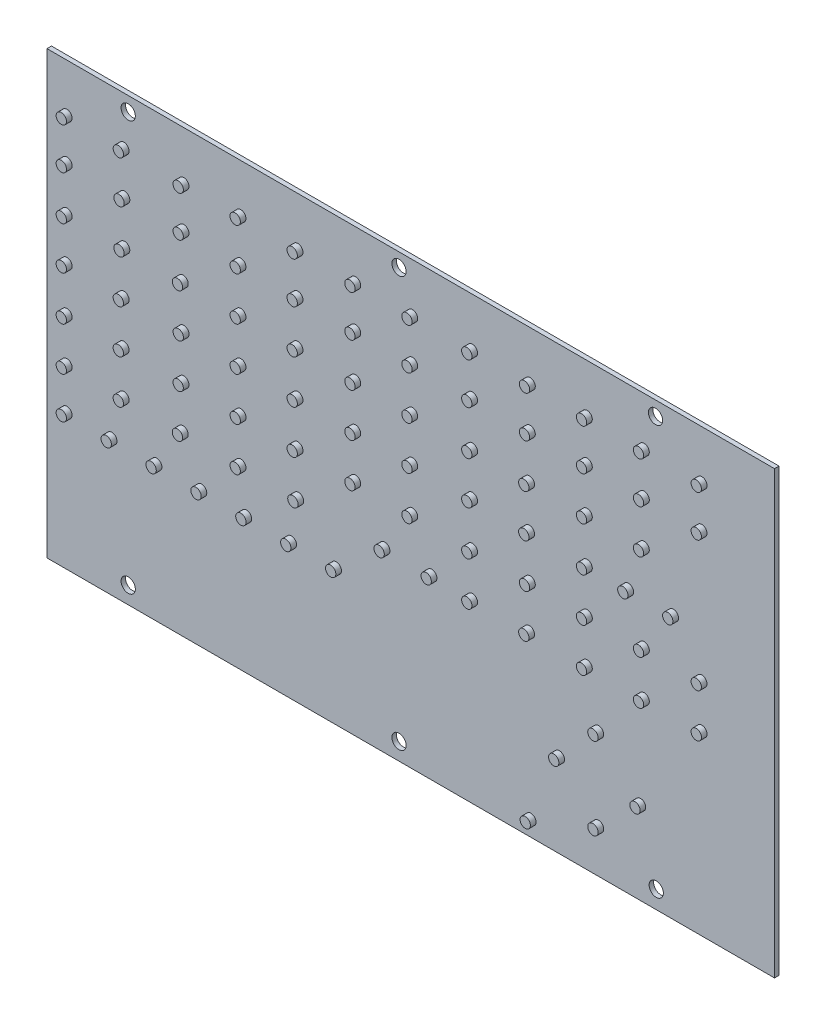
SolidWorks part; units mm, degrees
ref_plane "前视基准面" through (0, 0, 0) normal (0, 0, 1) x (1, 0, 0)
ref_plane "上视基准面" through (0, 0, 0) normal (0, 1, 0) x (1, 0, 0)
ref_plane "右视基准面" through (0, 0, 0) normal (1, 0, 0) x (0, 0, -1)
sketch "Model" plane through (0, 0, 0) normal (0, 0, 1) x (1, 0, 0)
  line L0 (148.209, 80.518) -> (148.1252, 80.518)
  line L1 (148.1252, 80.518) -> (134.874, 80.518)
  line L2 (134.874, 80.518) -> (18.542, 80.518)
  line L3 (101.092, 1.905) -> (18.542, 1.905)
  line L4 (18.542, 80.518) -> (18.542, 79.375)
  line L5 (18.542, 79.375) -> (18.542, 1.905)
  line L6 (18.542, 1.905) -> (18.763, 1.905)
  line L7 (148.209, 80.4342) -> (148.209, 80.518)
  line L8 (148.209, 80.518) -> (148.209, 1.905)
  line L9 (107.823, 1.905) -> (148.209, 1.905)
  line L10 (101.092, 1.905) -> (101.854, 1.905)
  line L11 (101.854, 1.905) -> (107.823, 1.905)
  line L12 (115.8771, 79.7949) -> (115.8771, 68.795)
  line L13 (121.1273, 79.7949) -> (115.8771, 79.7949)
  line L14 (121.1274, 68.7948) -> (115.8771, 68.7949)
  line L15 (121.1274, 68.7948) -> (121.427, 68.7948)
  line L16 (121.427, 68.7948) -> (121.427, 72.2638)
  line L17 (121.427, 76.326) -> (121.427, 79.805)
  line L18 (121.427, 79.805) -> (121.1273, 79.805)
  line L19 (140.208, 32.258) -> (142.7226, 32.258)
  line L20 (142.7226, 32.258) -> (142.7226, 27.178)
  line L21 (142.7226, 27.178) -> (140.208, 27.178)
  line L22 (140.208, 27.178) -> (140.208, 32.258)
  line L23 (143.891, 74.93) -> (143.891, 72.4154)
  line L24 (143.891, 72.4154) -> (138.811, 72.4154)
  line L25 (138.811, 72.4154) -> (138.811, 74.93)
  line L26 (138.811, 74.93) -> (143.891, 74.93)
  line L27 (130.2317, 51.816) -> (136.525, 45.5227)
  line L28 (136.525, 45.5227) -> (142.8183, 51.816)
  line L29 (142.8183, 51.816) -> (136.525, 58.1093)
  line L30 (136.525, 58.1093) -> (130.2317, 51.816)
  line L31 (144.146, 43.907) -> (144.146, 42.707)
  line L32 (146.196, 44.107) -> (147.196, 44.107)
  line L33 (146.196, 42.507) -> (147.196, 42.507)
  line L34 (145.3959, 44.107) -> (144.396, 44.107)
  line L35 (145.3959, 42.507) -> (144.396, 42.507)
  line L36 (147.446, 43.907) -> (147.446, 42.707)
  line L37 (147.246, 44.107) -> (147.196, 44.107)
  line L38 (147.246, 42.507) -> (147.196, 42.507)
  line L39 (144.346, 44.107) -> (144.396, 44.107)
  line L40 (144.346, 42.507) -> (144.396, 42.507)
  line L41 (144.146, 41.875) -> (144.146, 40.675)
  line L42 (146.196, 42.075) -> (147.196, 42.075)
  line L43 (146.196, 40.475) -> (147.196, 40.475)
  line L44 (145.3959, 42.075) -> (144.396, 42.075)
  line L45 (145.3959, 40.475) -> (144.396, 40.475)
  line L46 (147.446, 41.875) -> (147.446, 40.675)
  line L47 (147.246, 42.075) -> (147.196, 42.075)
  line L48 (147.246, 40.475) -> (147.196, 40.475)
  line L49 (144.346, 42.075) -> (144.396, 42.075)
  line L50 (144.346, 40.475) -> (144.396, 40.475)
  line L51 (144.146, 47.844) -> (144.146, 46.644)
  line L52 (146.196, 48.044) -> (147.196, 48.044)
  line L53 (146.196, 46.444) -> (147.196, 46.444)
  line L54 (145.3959, 48.044) -> (144.396, 48.044)
  line L55 (145.3959, 46.444) -> (144.396, 46.444)
  line L56 (147.446, 47.844) -> (147.446, 46.644)
  line L57 (147.246, 48.044) -> (147.196, 48.044)
  line L58 (147.246, 46.444) -> (147.196, 46.444)
  line L59 (144.346, 48.044) -> (144.396, 48.044)
  line L60 (144.346, 46.444) -> (144.396, 46.444)
  line L61 (144.146, 45.812) -> (144.146, 44.612)
  line L62 (146.196, 46.012) -> (147.196, 46.012)
  line L63 (146.196, 44.412) -> (147.196, 44.412)
  line L64 (145.3959, 46.012) -> (144.396, 46.012)
  line L65 (145.3959, 44.412) -> (144.396, 44.412)
  line L66 (147.446, 45.812) -> (147.446, 44.612)
  line L67 (147.246, 46.012) -> (147.196, 46.012)
  line L68 (147.246, 44.412) -> (147.196, 44.412)
  line L69 (144.346, 46.012) -> (144.396, 46.012)
  line L70 (144.346, 44.412) -> (144.396, 44.412)
  line L71 (139.061, 65.905) -> (139.061, 67.155)
  line L72 (141.101, 65.905) -> (141.101, 67.155)
  line L73 (139.061, 64.905) -> (139.061, 63.655)
  line L74 (141.101, 64.905) -> (141.101, 63.655)
  line L75 (139.061, 67.155) -> (141.101, 67.155)
  line L76 (139.061, 63.655) -> (141.101, 63.655)
  line L77 (141.347, 65.905) -> (141.347, 67.155)
  line L78 (143.387, 65.905) -> (143.387, 67.155)
  line L79 (141.347, 64.905) -> (141.347, 63.655)
  line L80 (143.387, 64.905) -> (143.387, 63.655)
  line L81 (141.347, 67.155) -> (143.387, 67.155)
  line L82 (141.347, 63.655) -> (143.387, 63.655)
  line L83 (132.426, 64.261) -> (131.226, 64.261)
  line L84 (132.626, 62.211) -> (132.626, 61.211)
  line L85 (131.026, 62.211) -> (131.026, 61.211)
  line L86 (132.626, 63.0111) -> (132.626, 64.011)
  line L87 (131.026, 63.0111) -> (131.026, 64.011)
  line L88 (132.426, 60.961) -> (131.226, 60.961)
  line L89 (132.626, 61.161) -> (132.626, 61.211)
  line L90 (131.026, 61.161) -> (131.026, 61.211)
  line L91 (132.626, 64.061) -> (132.626, 64.011)
  line L92 (131.026, 64.061) -> (131.026, 64.011)
  line L93 (143.983, 60.451) -> (142.783, 60.451)
  line L94 (144.183, 58.401) -> (144.183, 57.401)
  line L95 (142.583, 58.401) -> (142.583, 57.401)
  line L96 (144.183, 59.2011) -> (144.183, 60.201)
  line L97 (142.583, 59.2011) -> (142.583, 60.201)
  line L98 (143.983, 57.151) -> (142.783, 57.151)
  line L99 (144.183, 57.351) -> (144.183, 57.401)
  line L100 (142.583, 57.351) -> (142.583, 57.401)
  line L101 (144.183, 60.251) -> (144.183, 60.201)
  line L102 (142.583, 60.251) -> (142.583, 60.201)
  line L103 (139.354, 34.164) -> (140.554, 34.164)
  line L104 (139.154, 36.214) -> (139.154, 37.214)
  line L105 (140.754, 36.214) -> (140.754, 37.214)
  line L106 (139.154, 35.4139) -> (139.154, 34.414)
  line L107 (140.754, 35.4139) -> (140.754, 34.414)
  line L108 (139.354, 37.464) -> (140.554, 37.464)
  line L109 (139.154, 37.264) -> (139.154, 37.214)
  line L110 (140.754, 37.264) -> (140.754, 37.214)
  line L111 (139.154, 34.364) -> (139.154, 34.414)
  line L112 (140.754, 34.364) -> (140.754, 34.414)
  line L113 (141.513, 34.164) -> (142.713, 34.164)
  line L114 (141.313, 36.214) -> (141.313, 37.214)
  line L115 (142.913, 36.214) -> (142.913, 37.214)
  line L116 (141.313, 35.4139) -> (141.313, 34.414)
  line L117 (142.913, 35.4139) -> (142.913, 34.414)
  line L118 (141.513, 37.464) -> (142.713, 37.464)
  line L119 (141.313, 37.264) -> (141.313, 37.214)
  line L120 (142.913, 37.264) -> (142.913, 37.214)
  line L121 (141.313, 34.364) -> (141.313, 34.414)
  line L122 (142.913, 34.364) -> (142.913, 34.414)
  line L123 (145.5953, 81.4659) -> (145.9814, 81.885)
  line L124 (145.9814, 81.885) -> (145.6893, 81.885)
  line L125 (145.6893, 81.885) -> (145.0797, 81.2246)
  line L126 (145.0797, 81.2246) -> (138.065, 81.2246)
  line L127 (138.065, 81.2246) -> (137.4013, 81.9358)
  line L128 (137.4013, 81.9358) -> (137.2362, 81.9358)
  line L129 (137.2362, 81.9358) -> (137.2362, 81.885)
  line L130 (137.2362, 81.885) -> (137.5943, 81.4659)
  line L131 (137.6045, 75.9643) -> (139.8473, 75.9643)
  line L132 (143.3627, 75.9643) -> (145.6055, 75.9643)
  line L133 (145.6055, 79.9953) -> (145.6055, 81.5879)
  line L134 (137.6045, 79.9953) -> (137.6045, 81.4659)
  line L135 (137.6045, 79.9953) -> (137.6045, 79.9305)
  line L136 (137.6045, 78.1682) -> (137.6045, 77.3765)
  line L137 (137.6045, 76.0142) -> (137.6045, 75.9643)
  line L138 (145.6055, 79.9953) -> (145.6055, 79.9305)
  line L139 (145.6055, 78.1682) -> (145.6055, 77.3765)
  line L140 (145.6055, 76.0142) -> (145.6055, 75.9643)
  line L141 (138.9969, 41.8319) -> (143.1969, 41.8319)
  line L142 (143.1969, 41.8319) -> (143.1969, 38.4319)
  line L143 (143.1969, 38.4319) -> (138.9969, 38.4319)
  line L144 (138.9969, 38.4319) -> (138.9969, 41.8319)
  line L145 (20.823, 74.2591) -> (23.373, 74.2591)
  line L146 (24.348, 73.1779) -> (24.348, 70.8401)
  line L147 (23.3728, 69.7591) -> (20.8232, 69.7591)
  line L148 (19.848, 70.8401) -> (19.848, 73.1779)
  line L149 (20.823, 66.8931) -> (23.373, 66.8931)
  line L150 (24.348, 65.8119) -> (24.348, 63.4741)
  line L151 (23.3728, 62.3931) -> (20.8232, 62.3931)
  line L152 (19.848, 63.4741) -> (19.848, 65.8119)
  line L153 (20.823, 59.0191) -> (23.373, 59.0191)
  line L154 (24.348, 57.9379) -> (24.348, 55.6001)
  line L155 (23.3728, 54.5191) -> (20.8232, 54.5191)
  line L156 (19.848, 55.6001) -> (19.848, 57.9379)
  line L157 (20.823, 51.3991) -> (23.373, 51.3991)
  line L158 (24.348, 50.3179) -> (24.348, 47.9801)
  line L159 (23.3728, 46.8991) -> (20.8232, 46.8991)
  line L160 (19.848, 47.9801) -> (19.848, 50.3179)
  line L161 (20.823, 43.5251) -> (23.373, 43.5251)
  line L162 (24.348, 42.4439) -> (24.348, 40.1061)
  line L163 (23.3728, 39.0251) -> (20.8232, 39.0251)
  line L164 (19.848, 40.1061) -> (19.848, 42.4439)
  line L165 (20.823, 35.7781) -> (23.373, 35.7781)
  line L166 (24.348, 34.6969) -> (24.348, 32.3591)
  line L167 (23.3728, 31.2781) -> (20.8232, 31.2781)
  line L168 (19.848, 32.3591) -> (19.848, 34.6969)
  line L169 (20.823, 28.4121) -> (23.373, 28.4121)
  line L170 (24.348, 27.3309) -> (24.348, 24.9931)
  line L171 (23.3728, 23.9121) -> (20.8232, 23.9121)
  line L172 (19.848, 24.9931) -> (19.848, 27.3309)
  line L173 (28.824, 28.4121) -> (31.374, 28.4121)
  line L174 (32.349, 27.3309) -> (32.349, 24.9931)
  line L175 (31.3738, 23.9121) -> (28.8242, 23.9121)
  line L176 (27.849, 24.9931) -> (27.849, 27.3309)
  line L177 (30.983, 35.7781) -> (33.533, 35.7781)
  line L178 (34.508, 34.6969) -> (34.508, 32.3591)
  line L179 (33.5328, 31.2781) -> (30.9832, 31.2781)
  line L180 (30.008, 32.3591) -> (30.008, 34.6969)
  line L181 (30.983, 43.5251) -> (33.533, 43.5251)
  line L182 (34.508, 42.4439) -> (34.508, 40.1061)
  line L183 (33.5328, 39.0251) -> (30.9832, 39.0251)
  line L184 (30.008, 40.1061) -> (30.008, 42.4439)
  line L185 (30.983, 51.2721) -> (33.533, 51.2721)
  line L186 (34.508, 50.1909) -> (34.508, 47.8531)
  line L187 (33.5328, 46.7721) -> (30.9832, 46.7721)
  line L188 (30.008, 47.8531) -> (30.008, 50.1909)
  line L189 (31.11, 59.0191) -> (33.66, 59.0191)
  line L190 (34.635, 57.9379) -> (34.635, 55.6001)
  line L191 (33.6598, 54.5191) -> (31.1102, 54.5191)
  line L192 (30.135, 55.6001) -> (30.135, 57.9379)
  line L193 (31.11, 66.7661) -> (33.66, 66.7661)
  line L194 (34.635, 65.6849) -> (34.635, 63.3471)
  line L195 (33.6598, 62.2661) -> (31.1102, 62.2661)
  line L196 (30.135, 63.3471) -> (30.135, 65.6849)
  line L197 (30.983, 74.2591) -> (33.533, 74.2591)
  line L198 (34.508, 73.1779) -> (34.508, 70.8401)
  line L199 (33.5328, 69.7591) -> (30.9832, 69.7591)
  line L200 (30.008, 70.8401) -> (30.008, 73.1779)
  line L201 (36.825, 28.4121) -> (39.375, 28.4121)
  line L202 (40.35, 27.3309) -> (40.35, 24.9931)
  line L203 (39.3748, 23.9121) -> (36.8252, 23.9121)
  line L204 (35.85, 24.9931) -> (35.85, 27.3309)
  line L205 (41.524, 35.7781) -> (44.074, 35.7781)
  line L206 (45.049, 34.6969) -> (45.049, 32.3591)
  line L207 (44.0738, 31.2781) -> (41.5242, 31.2781)
  line L208 (40.549, 32.3591) -> (40.549, 34.6969)
  line L209 (41.651, 43.5251) -> (44.201, 43.5251)
  line L210 (45.176, 42.4439) -> (45.176, 40.1061)
  line L211 (44.2008, 39.0251) -> (41.6512, 39.0251)
  line L212 (40.676, 40.1061) -> (40.676, 42.4439)
  line L213 (41.651, 51.2721) -> (44.201, 51.2721)
  line L214 (45.176, 50.1909) -> (45.176, 47.8531)
  line L215 (44.2008, 46.7721) -> (41.6512, 46.7721)
  line L216 (40.676, 47.8531) -> (40.676, 50.1909)
  line L217 (41.524, 59.0191) -> (44.074, 59.0191)
  line L218 (45.049, 57.9379) -> (45.049, 55.6001)
  line L219 (44.0738, 54.5191) -> (41.5242, 54.5191)
  line L220 (40.549, 55.6001) -> (40.549, 57.9379)
  line L221 (41.651, 66.8931) -> (44.201, 66.8931)
  line L222 (45.176, 65.8119) -> (45.176, 63.4741)
  line L223 (44.2008, 62.3931) -> (41.6512, 62.3931)
  line L224 (40.676, 63.4741) -> (40.676, 65.8119)
  line L225 (41.651, 74.1321) -> (44.201, 74.1321)
  line L226 (45.176, 73.0509) -> (45.176, 70.7131)
  line L227 (44.2008, 69.6321) -> (41.6512, 69.6321)
  line L228 (40.676, 70.7131) -> (40.676, 73.0509)
  line L229 (44.826, 28.4121) -> (47.376, 28.4121)
  line L230 (48.351, 27.3309) -> (48.351, 24.9931)
  line L231 (47.3758, 23.9121) -> (44.8262, 23.9121)
  line L232 (43.851, 24.9931) -> (43.851, 27.3309)
  line L233 (51.811, 35.7781) -> (54.361, 35.7781)
  line L234 (55.336, 34.6969) -> (55.336, 32.3591)
  line L235 (54.3608, 31.2781) -> (51.8112, 31.2781)
  line L236 (50.836, 32.3591) -> (50.836, 34.6969)
  line L237 (51.811, 43.5251) -> (54.361, 43.5251)
  line L238 (55.336, 42.4439) -> (55.336, 40.1061)
  line L239 (54.3608, 39.0251) -> (51.8112, 39.0251)
  line L240 (50.836, 40.1061) -> (50.836, 42.4439)
  line L241 (51.811, 51.2721) -> (54.361, 51.2721)
  line L242 (55.336, 50.1909) -> (55.336, 47.8531)
  line L243 (54.3608, 46.7721) -> (51.8112, 46.7721)
  line L244 (50.836, 47.8531) -> (50.836, 50.1909)
  line L245 (51.811, 59.0191) -> (54.361, 59.0191)
  line L246 (55.336, 57.9379) -> (55.336, 55.6001)
  line L247 (54.3608, 54.5191) -> (51.8112, 54.5191)
  line L248 (50.836, 55.6001) -> (50.836, 57.9379)
  line L249 (51.811, 66.7661) -> (54.361, 66.7661)
  line L250 (55.336, 65.6849) -> (55.336, 63.3471)
  line L251 (54.3608, 62.2661) -> (51.8112, 62.2661)
  line L252 (50.836, 63.3471) -> (50.836, 65.6849)
  line L253 (51.811, 74.2591) -> (54.361, 74.2591)
  line L254 (55.336, 73.1779) -> (55.336, 70.8401)
  line L255 (54.3608, 69.7591) -> (51.8112, 69.7591)
  line L256 (50.836, 70.8401) -> (50.836, 73.1779)
  line L257 (52.827, 28.4121) -> (55.377, 28.4121)
  line L258 (56.352, 27.3309) -> (56.352, 24.9931)
  line L259 (55.3768, 23.9121) -> (52.8272, 23.9121)
  line L260 (51.852, 24.9931) -> (51.852, 27.3309)
  line L261 (62.098, 35.7781) -> (64.648, 35.7781)
  line L262 (65.623, 34.6969) -> (65.623, 32.3591)
  line L263 (64.6478, 31.2781) -> (62.0982, 31.2781)
  line L264 (61.123, 32.3591) -> (61.123, 34.6969)
  line L265 (61.971, 43.5251) -> (64.521, 43.5251)
  line L266 (65.496, 42.4439) -> (65.496, 40.1061)
  line L267 (64.5208, 39.0251) -> (61.9712, 39.0251)
  line L268 (60.996, 40.1061) -> (60.996, 42.4439)
  line L269 (61.971, 51.2721) -> (64.521, 51.2721)
  line L270 (65.496, 50.1909) -> (65.496, 47.8531)
  line L271 (64.5208, 46.7721) -> (61.9712, 46.7721)
  line L272 (60.996, 47.8531) -> (60.996, 50.1909)
  line L273 (61.971, 59.0191) -> (64.521, 59.0191)
  line L274 (65.496, 57.9379) -> (65.496, 55.6001)
  line L275 (64.5208, 54.5191) -> (61.9712, 54.5191)
  line L276 (60.996, 55.6001) -> (60.996, 57.9379)
  line L277 (61.971, 66.7661) -> (64.521, 66.7661)
  line L278 (65.496, 65.6849) -> (65.496, 63.3471)
  line L279 (64.5208, 62.2661) -> (61.9712, 62.2661)
  line L280 (60.996, 63.3471) -> (60.996, 65.6849)
  line L281 (61.971, 74.1321) -> (64.521, 74.1321)
  line L282 (65.496, 73.0509) -> (65.496, 70.7131)
  line L283 (64.5208, 69.6321) -> (61.9712, 69.6321)
  line L284 (60.996, 70.7131) -> (60.996, 73.0509)
  line L285 (60.828, 28.4121) -> (63.378, 28.4121)
  line L286 (64.353, 27.3309) -> (64.353, 24.9931)
  line L287 (63.3778, 23.9121) -> (60.8282, 23.9121)
  line L288 (59.853, 24.9931) -> (59.853, 27.3309)
  line L289 (77.465, 35.7781) -> (80.015, 35.7781)
  line L290 (80.99, 34.6969) -> (80.99, 32.3591)
  line L291 (80.0148, 31.2781) -> (77.4652, 31.2781)
  line L292 (76.49, 32.3591) -> (76.49, 34.6969)
  line L293 (72.258, 43.5251) -> (74.808, 43.5251)
  line L294 (75.783, 42.4439) -> (75.783, 40.1061)
  line L295 (74.8078, 39.0251) -> (72.2582, 39.0251)
  line L296 (71.283, 40.1061) -> (71.283, 42.4439)
  line L297 (72.258, 51.2721) -> (74.808, 51.2721)
  line L298 (75.783, 50.1909) -> (75.783, 47.8531)
  line L299 (74.8078, 46.7721) -> (72.2582, 46.7721)
  line L300 (71.283, 47.8531) -> (71.283, 50.1909)
  line L301 (72.258, 59.0191) -> (74.808, 59.0191)
  line L302 (75.783, 57.9379) -> (75.783, 55.6001)
  line L303 (74.8078, 54.5191) -> (72.2582, 54.5191)
  line L304 (71.283, 55.6001) -> (71.283, 57.9379)
  line L305 (72.258, 66.7661) -> (74.808, 66.7661)
  line L306 (75.783, 65.6849) -> (75.783, 63.3471)
  line L307 (74.8078, 62.2661) -> (72.2582, 62.2661)
  line L308 (71.283, 63.3471) -> (71.283, 65.6849)
  line L309 (72.258, 74.1321) -> (74.808, 74.1321)
  line L310 (75.783, 73.0509) -> (75.783, 70.7131)
  line L311 (74.8078, 69.6321) -> (72.2582, 69.6321)
  line L312 (71.283, 70.7131) -> (71.283, 73.0509)
  line L313 (68.829, 28.4121) -> (71.379, 28.4121)
  line L314 (72.354, 27.3309) -> (72.354, 24.9931)
  line L315 (71.3788, 23.9121) -> (68.8292, 23.9121)
  line L316 (67.854, 24.9931) -> (67.854, 27.3309)
  line L317 (85.847, 35.7781) -> (88.397, 35.7781)
  line L318 (89.372, 34.6969) -> (89.372, 32.3591)
  line L319 (88.3968, 31.2781) -> (85.8472, 31.2781)
  line L320 (84.872, 32.3591) -> (84.872, 34.6969)
  line L321 (82.418, 43.5251) -> (84.968, 43.5251)
  line L322 (85.943, 42.4439) -> (85.943, 40.1061)
  line L323 (84.9678, 39.0251) -> (82.4182, 39.0251)
  line L324 (81.443, 40.1061) -> (81.443, 42.4439)
  line L325 (82.418, 51.2721) -> (84.968, 51.2721)
  line L326 (85.943, 50.1909) -> (85.943, 47.8531)
  line L327 (84.9678, 46.7721) -> (82.4182, 46.7721)
  line L328 (81.443, 47.8531) -> (81.443, 50.1909)
  line L329 (82.418, 59.0191) -> (84.968, 59.0191)
  line L330 (85.943, 57.9379) -> (85.943, 55.6001)
  line L331 (84.9678, 54.5191) -> (82.4182, 54.5191)
  line L332 (81.443, 55.6001) -> (81.443, 57.9379)
  line L333 (82.418, 66.7661) -> (84.968, 66.7661)
  line L334 (85.943, 65.6849) -> (85.943, 63.3471)
  line L335 (84.9678, 62.2661) -> (82.4182, 62.2661)
  line L336 (81.443, 63.3471) -> (81.443, 65.6849)
  line L337 (82.418, 74.1321) -> (84.968, 74.1321)
  line L338 (85.943, 73.0509) -> (85.943, 70.7131)
  line L339 (84.9678, 69.6321) -> (82.4182, 69.6321)
  line L340 (81.443, 70.7131) -> (81.443, 73.0509)
  line L341 (103.5, 6.9491) -> (106.05, 6.9491)
  line L342 (107.025, 5.8679) -> (107.025, 3.5301)
  line L343 (106.0498, 2.4491) -> (103.5002, 2.4491)
  line L344 (102.525, 3.5301) -> (102.525, 5.8679)
  line L345 (93.086, 35.6511) -> (95.636, 35.6511)
  line L346 (96.611, 34.5699) -> (96.611, 32.2321)
  line L347 (95.6358, 31.1511) -> (93.0862, 31.1511)
  line L348 (92.111, 32.2321) -> (92.111, 34.5699)
  line L349 (93.086, 43.3981) -> (95.636, 43.3981)
  line L350 (96.611, 42.3169) -> (96.611, 39.9791)
  line L351 (95.6358, 38.8981) -> (93.0862, 38.8981)
  line L352 (92.111, 39.9791) -> (92.111, 42.3169)
  line L353 (93.086, 51.2721) -> (95.636, 51.2721)
  line L354 (96.611, 50.1909) -> (96.611, 47.8531)
  line L355 (95.6358, 46.7721) -> (93.0862, 46.7721)
  line L356 (92.111, 47.8531) -> (92.111, 50.1909)
  line L357 (93.086, 58.8921) -> (95.636, 58.8921)
  line L358 (96.611, 57.8109) -> (96.611, 55.4731)
  line L359 (95.6358, 54.3921) -> (93.0862, 54.3921)
  line L360 (92.111, 55.4731) -> (92.111, 57.8109)
  line L361 (93.086, 66.7661) -> (95.636, 66.7661)
  line L362 (96.611, 65.6849) -> (96.611, 63.3471)
  line L363 (95.6358, 62.2661) -> (93.0862, 62.2661)
  line L364 (92.111, 63.3471) -> (92.111, 65.6849)
  line L365 (93.086, 74.1321) -> (95.636, 74.1321)
  line L366 (96.611, 73.0509) -> (96.611, 70.7131)
  line L367 (95.6358, 69.6321) -> (93.0862, 69.6321)
  line L368 (92.111, 70.7131) -> (92.111, 73.0509)
  line L369 (108.58, 19.1411) -> (111.13, 19.1411)
  line L370 (112.105, 18.0599) -> (112.105, 15.7221)
  line L371 (111.1298, 14.6411) -> (108.5802, 14.6411)
  line L372 (107.605, 15.7221) -> (107.605, 18.0599)
  line L373 (103.246, 35.7781) -> (105.796, 35.7781)
  line L374 (106.771, 34.6969) -> (106.771, 32.3591)
  line L375 (105.7958, 31.2781) -> (103.2462, 31.2781)
  line L376 (102.271, 32.3591) -> (102.271, 34.6969)
  line L377 (103.373, 43.5251) -> (105.923, 43.5251)
  line L378 (106.898, 42.4439) -> (106.898, 40.1061)
  line L379 (105.9228, 39.0251) -> (103.3732, 39.0251)
  line L380 (102.398, 40.1061) -> (102.398, 42.4439)
  line L381 (103.246, 51.2721) -> (105.796, 51.2721)
  line L382 (106.771, 50.1909) -> (106.771, 47.8531)
  line L383 (105.7958, 46.7721) -> (103.2462, 46.7721)
  line L384 (102.271, 47.8531) -> (102.271, 50.1909)
  line L385 (103.246, 58.8921) -> (105.796, 58.8921)
  line L386 (106.771, 57.8109) -> (106.771, 55.4731)
  line L387 (105.7958, 54.3921) -> (103.2462, 54.3921)
  line L388 (102.271, 55.4731) -> (102.271, 57.8109)
  line L389 (103.373, 66.7661) -> (105.923, 66.7661)
  line L390 (106.898, 65.6849) -> (106.898, 63.3471)
  line L391 (105.9228, 62.2661) -> (103.3732, 62.2661)
  line L392 (102.398, 63.3471) -> (102.398, 65.6849)
  line L393 (103.373, 74.1321) -> (105.923, 74.1321)
  line L394 (106.898, 73.0509) -> (106.898, 70.7131)
  line L395 (105.9228, 69.6321) -> (103.3732, 69.6321)
  line L396 (102.398, 70.7131) -> (102.398, 73.0509)
  line L397 (115.565, 26.5071) -> (118.115, 26.5071)
  line L398 (119.09, 25.4259) -> (119.09, 23.0881)
  line L399 (118.1148, 22.0071) -> (115.5652, 22.0071)
  line L400 (114.59, 23.0881) -> (114.59, 25.4259)
  line L401 (113.533, 35.6511) -> (116.083, 35.6511)
  line L402 (117.058, 34.5699) -> (117.058, 32.2321)
  line L403 (116.0828, 31.1511) -> (113.5332, 31.1511)
  line L404 (112.558, 32.2321) -> (112.558, 34.5699)
  line L405 (113.533, 43.3981) -> (116.083, 43.3981)
  line L406 (117.058, 42.3169) -> (117.058, 39.9791)
  line L407 (116.0828, 38.8981) -> (113.5332, 38.8981)
  line L408 (112.558, 39.9791) -> (112.558, 42.3169)
  line L409 (113.533, 51.1451) -> (116.083, 51.1451)
  line L410 (117.058, 50.0639) -> (117.058, 47.7261)
  line L411 (116.0828, 46.6451) -> (113.5332, 46.6451)
  line L412 (112.558, 47.7261) -> (112.558, 50.0639)
  line L413 (113.533, 59.0191) -> (116.083, 59.0191)
  line L414 (117.058, 57.9379) -> (117.058, 55.6001)
  line L415 (116.0828, 54.5191) -> (113.5332, 54.5191)
  line L416 (112.558, 55.6001) -> (112.558, 57.9379)
  line L417 (113.533, 66.7661) -> (116.083, 66.7661)
  line L418 (117.058, 65.6849) -> (117.058, 63.3471)
  line L419 (116.0828, 62.2661) -> (113.5332, 62.2661)
  line L420 (112.558, 63.3471) -> (112.558, 65.6849)
  line L421 (113.533, 74.1321) -> (116.083, 74.1321)
  line L422 (117.058, 73.0509) -> (117.058, 70.7131)
  line L423 (116.0828, 69.6321) -> (113.5332, 69.6321)
  line L424 (112.558, 70.7131) -> (112.558, 73.0509)
  line L425 (123.058, 19.0141) -> (125.608, 19.0141)
  line L426 (126.583, 17.9329) -> (126.583, 15.5951)
  line L427 (125.6078, 14.5141) -> (123.0582, 14.5141)
  line L428 (122.083, 15.5951) -> (122.083, 17.9329)
  line L429 (123.693, 35.6511) -> (126.243, 35.6511)
  line L430 (127.218, 34.5699) -> (127.218, 32.2321)
  line L431 (126.2428, 31.1511) -> (123.6932, 31.1511)
  line L432 (122.718, 32.2321) -> (122.718, 34.5699)
  line L433 (123.693, 43.5251) -> (126.243, 43.5251)
  line L434 (127.218, 42.4439) -> (127.218, 40.1061)
  line L435 (126.2428, 39.0251) -> (123.6932, 39.0251)
  line L436 (122.718, 40.1061) -> (122.718, 42.4439)
  line L437 (120.899, 51.1451) -> (123.449, 51.1451)
  line L438 (124.424, 50.0639) -> (124.424, 47.7261)
  line L439 (123.4488, 46.6451) -> (120.8992, 46.6451)
  line L440 (119.924, 47.7261) -> (119.924, 50.0639)
  line L441 (123.693, 59.0191) -> (126.243, 59.0191)
  line L442 (127.218, 57.9379) -> (127.218, 55.6001)
  line L443 (126.2428, 54.5191) -> (123.6932, 54.5191)
  line L444 (122.718, 55.6001) -> (122.718, 57.9379)
  line L445 (123.693, 66.7661) -> (126.243, 66.7661)
  line L446 (127.218, 65.6849) -> (127.218, 63.3471)
  line L447 (126.2428, 62.2661) -> (123.6932, 62.2661)
  line L448 (122.718, 63.3471) -> (122.718, 65.6849)
  line L449 (123.693, 74.1321) -> (126.243, 74.1321)
  line L450 (127.218, 73.0509) -> (127.218, 70.7131)
  line L451 (126.2428, 69.6321) -> (123.6932, 69.6321)
  line L452 (122.718, 70.7131) -> (122.718, 73.0509)
  line L453 (115.565, 11.9021) -> (118.115, 11.9021)
  line L454 (119.09, 10.8209) -> (119.09, 8.4831)
  line L455 (118.1148, 7.4021) -> (115.5652, 7.4021)
  line L456 (114.59, 8.4831) -> (114.59, 10.8209)
  line L457 (133.98, 35.7781) -> (136.53, 35.7781)
  line L458 (137.505, 34.6969) -> (137.505, 32.3591)
  line L459 (136.5298, 31.2781) -> (133.9802, 31.2781)
  line L460 (133.005, 32.3591) -> (133.005, 34.6969)
  line L461 (133.98, 43.5251) -> (136.53, 43.5251)
  line L462 (137.505, 42.4439) -> (137.505, 40.1061)
  line L463 (136.5298, 39.0251) -> (133.9802, 39.0251)
  line L464 (133.005, 40.1061) -> (133.005, 42.4439)
  line L465 (128.9, 51.1451) -> (131.45, 51.1451)
  line L466 (132.425, 50.0639) -> (132.425, 47.7261)
  line L467 (131.4498, 46.6451) -> (128.9002, 46.6451)
  line L468 (127.925, 47.7261) -> (127.925, 50.0639)
  line L469 (133.98, 58.8921) -> (136.53, 58.8921)
  line L470 (137.505, 57.8109) -> (137.505, 55.4731)
  line L471 (136.5298, 54.3921) -> (133.9802, 54.3921)
  line L472 (133.005, 55.4731) -> (133.005, 57.8109)
  line L473 (133.98, 66.7661) -> (136.53, 66.7661)
  line L474 (137.505, 65.6849) -> (137.505, 63.3471)
  line L475 (136.5298, 62.2661) -> (133.9802, 62.2661)
  line L476 (133.005, 63.3471) -> (133.005, 65.6849)
  line L477 (133.98, 74.1321) -> (136.53, 74.1321)
  line L478 (137.505, 73.0509) -> (137.505, 70.7131)
  line L479 (136.5298, 69.6321) -> (133.9802, 69.6321)
  line L480 (133.005, 70.7131) -> (133.005, 73.0509)
  line L481 (28.575, 19.05) -> (28.575, 7.62)
  line L482 (28.575, 7.62) -> (47.625, 7.62)
  line L483 (47.625, 7.62) -> (66.675, 7.62)
  line L484 (66.675, 7.62) -> (66.7748, 19.5199)
  line L485 (66.7748, 19.5199) -> (28.575, 19.5199)
  line L486 (28.575, 19.5199) -> (28.575, 19.05)
  line L487 (131.191, 71.12) -> (128.6764, 71.12)
  line L488 (128.6764, 71.12) -> (128.6764, 66.04)
  line L489 (128.6764, 66.04) -> (131.191, 66.04)
  line L490 (131.191, 66.04) -> (131.191, 71.12)
  line L491 (120.6769, 75.4949) -> (120.6769, 76.0949)
  line L492 (120.6769, 76.0949) -> (122.8769, 76.0949)
  line L493 (122.8769, 76.0949) -> (122.8769, 75.4949)
  line L494 (122.8769, 75.4949) -> (120.6769, 75.4949)
  line L495 (120.6769, 74.4949) -> (120.6769, 75.0949)
  line L496 (120.6769, 75.0949) -> (122.8769, 75.0949)
  line L497 (122.8769, 75.0949) -> (122.8769, 74.4949)
  line L498 (122.8769, 74.4949) -> (120.6769, 74.4949)
  line L499 (120.6769, 73.4949) -> (120.6769, 74.0949)
  line L500 (120.6769, 74.0949) -> (122.8769, 74.0949)
  line L501 (122.8769, 74.0949) -> (122.8769, 73.4949)
  line L502 (122.8769, 73.4949) -> (120.6769, 73.4949)
  line L503 (120.6769, 72.4949) -> (120.6769, 73.0949)
  line L504 (120.6769, 73.0949) -> (122.8769, 73.0949)
  line L505 (122.8769, 73.0949) -> (122.8769, 72.4949)
  line L506 (122.8769, 72.4949) -> (120.6769, 72.4949)
  line L507 (121.0769, 69.1949) -> (121.0769, 71.7949)
  line L508 (121.0769, 71.7949) -> (118.477, 71.7949)
  line L509 (118.477, 71.7949) -> (118.477, 69.1949)
  line L510 (118.477, 69.1949) -> (121.0769, 69.1949)
  line L511 (121.0769, 76.7949) -> (121.0769, 79.3949)
  line L512 (121.0769, 79.3949) -> (118.477, 79.3949)
  line L513 (118.477, 79.3949) -> (118.477, 76.7949)
  line L514 (118.477, 76.7949) -> (121.0769, 76.7949)
  line L515 (140.6906, 29.2354) -> (142.2654, 29.2354)
  line L516 (142.2654, 29.2354) -> (142.2654, 27.6606)
  line L517 (142.2654, 27.6606) -> (140.6906, 27.6606)
  line L518 (140.6906, 27.6606) -> (140.6906, 29.2354)
  line L519 (140.8684, 74.4474) -> (140.8684, 72.8726)
  line L520 (140.8684, 72.8726) -> (139.2936, 72.8726)
  line L521 (139.2936, 72.8726) -> (139.2936, 74.4474)
  line L522 (139.2936, 74.4474) -> (140.8684, 74.4474)
  line L523 (137.1259, 58.3707) -> (137.9603, 59.2051)
  line L524 (137.9603, 59.2051) -> (137.1259, 58.3707)
  line L525 (137.4229, 58.0738) -> (138.2573, 58.9082)
  line L526 (138.2573, 58.9082) -> (137.4229, 58.0738)
  line L527 (137.6918, 57.8051) -> (138.5262, 58.6395)
  line L528 (138.5262, 58.6395) -> (137.6918, 57.8051)
  line L529 (137.9888, 57.5081) -> (138.8232, 58.3425)
  line L530 (138.8232, 58.3425) -> (137.9888, 57.5081)
  line L531 (138.2573, 57.2394) -> (139.0916, 58.0738)
  line L532 (139.0916, 58.0738) -> (138.2573, 57.2394)
  line L533 (138.5542, 56.9425) -> (139.3886, 57.7768)
  line L534 (139.3886, 57.7768) -> (138.5542, 56.9425)
  line L535 (138.8232, 56.6738) -> (139.6576, 57.5082)
  line L536 (139.6576, 57.5082) -> (138.8232, 56.6738)
  line L537 (139.1201, 56.3768) -> (139.9545, 57.2112)
  line L538 (139.9545, 57.2112) -> (139.1201, 56.3768)
  line L539 (139.3886, 56.1081) -> (140.223, 56.9425)
  line L540 (140.223, 56.9425) -> (139.3886, 56.1081)
  line L541 (139.6855, 55.8111) -> (140.5199, 56.6455)
  line L542 (140.5199, 56.6455) -> (139.6855, 55.8111)
  line L543 (139.9545, 55.5425) -> (140.7889, 56.3769)
  line L544 (140.7889, 56.3769) -> (139.9545, 55.5425)
  line L545 (140.2515, 55.2455) -> (141.0859, 56.0799)
  line L546 (141.0859, 56.0799) -> (140.2515, 55.2455)
  line L547 (140.5201, 54.9765) -> (141.3545, 55.8109)
  line L548 (141.3545, 55.8109) -> (140.5201, 54.9765)
  line L549 (140.8171, 54.6796) -> (141.6515, 55.514)
  line L550 (141.6515, 55.514) -> (140.8171, 54.6796)
  line L551 (141.0858, 54.4111) -> (141.9202, 55.2455)
  line L552 (141.9202, 55.2455) -> (141.0858, 54.4111)
  line L553 (141.3828, 54.1142) -> (142.2172, 54.9486)
  line L554 (142.2172, 54.9486) -> (141.3828, 54.1142)
  line L555 (141.6515, 53.8452) -> (142.4858, 54.6796)
  line L556 (142.4858, 54.6796) -> (141.6515, 53.8452)
  line L557 (141.9484, 53.5483) -> (142.7828, 54.3826)
  line L558 (142.7828, 54.3826) -> (141.9484, 53.5483)
  line L559 (142.2171, 53.2798) -> (143.0515, 54.1142)
  line L560 (143.0515, 54.1142) -> (142.2171, 53.2798)
  line L561 (142.5141, 52.9828) -> (143.3485, 53.8172)
  line L562 (143.3485, 53.8172) -> (142.5141, 52.9828)
  line L563 (142.7828, 52.7139) -> (143.6172, 53.5483)
  line L564 (143.6172, 53.5483) -> (142.7828, 52.7139)
  line L565 (143.0797, 52.4169) -> (143.9141, 53.2513)
  line L566 (143.9141, 53.2513) -> (143.0797, 52.4169)
  line L567 (143.6172, 50.0837) -> (142.7828, 50.9181)
  line L568 (142.7828, 50.9181) -> (143.6172, 50.0837)
  line L569 (143.9141, 50.3807) -> (143.0797, 51.2151)
  line L570 (143.0797, 51.2151) -> (143.9141, 50.3807)
  line L571 (143.0515, 49.5178) -> (142.2171, 50.3522)
  line L572 (142.2171, 50.3522) -> (143.0515, 49.5178)
  line L573 (143.3485, 49.8148) -> (142.5141, 50.6492)
  line L574 (142.5141, 50.6492) -> (143.3485, 49.8148)
  line L575 (142.4858, 48.9524) -> (141.6515, 49.7868)
  line L576 (141.6515, 49.7868) -> (142.4858, 48.9524)
  line L577 (142.7828, 49.2494) -> (141.9484, 50.0837)
  line L578 (141.9484, 50.0837) -> (142.7828, 49.2494)
  line L579 (141.9202, 48.3865) -> (141.0858, 49.2209)
  line L580 (141.0858, 49.2209) -> (141.9202, 48.3865)
  line L581 (142.2172, 48.6834) -> (141.3828, 49.5178)
  line L582 (141.3828, 49.5178) -> (142.2172, 48.6834)
  line L583 (141.3545, 47.8208) -> (140.5201, 48.6552)
  line L584 (140.5201, 48.6552) -> (141.3545, 47.8208)
  line L585 (141.6515, 48.1178) -> (140.8171, 48.9522)
  line L586 (140.8171, 48.9522) -> (141.6515, 48.1178)
  line L587 (140.7889, 47.2551) -> (139.9545, 48.0895)
  line L588 (139.9545, 48.0895) -> (140.7889, 47.2551)
  line L589 (141.0859, 47.5521) -> (140.2515, 48.3865)
  line L590 (140.2515, 48.3865) -> (141.0859, 47.5521)
  line L591 (140.223, 46.6895) -> (139.3886, 47.5239)
  line L592 (139.3886, 47.5239) -> (140.223, 46.6895)
  line L593 (140.5199, 46.9865) -> (139.6855, 47.8209)
  line L594 (139.6855, 47.8209) -> (140.5199, 46.9865)
  line L595 (139.6576, 46.1238) -> (138.8232, 46.9582)
  line L596 (138.8232, 46.9582) -> (139.6576, 46.1238)
  line L597 (139.9545, 46.4208) -> (139.1201, 47.2552)
  line L598 (139.1201, 47.2552) -> (139.9545, 46.4208)
  line L599 (139.0916, 45.5582) -> (138.2573, 46.3926)
  line L600 (138.2573, 46.3926) -> (139.0916, 45.5582)
  line L601 (139.3886, 45.8552) -> (138.5542, 46.6895)
  line L602 (138.5542, 46.6895) -> (139.3886, 45.8552)
  line L603 (138.5262, 44.9925) -> (137.6918, 45.8269)
  line L604 (137.6918, 45.8269) -> (138.5262, 44.9925)
  line L605 (138.8232, 45.2895) -> (137.9888, 46.1239)
  line L606 (137.9888, 46.1239) -> (138.8232, 45.2895)
  line L607 (137.9603, 44.4269) -> (137.1259, 45.2613)
  line L608 (137.1259, 45.2613) -> (137.9603, 44.4269)
  line L609 (138.2573, 44.7238) -> (137.4229, 45.5582)
  line L610 (137.4229, 45.5582) -> (138.2573, 44.7238)
  line L611 (134.7927, 44.7238) -> (135.6271, 45.5582)
  line L612 (135.6271, 45.5582) -> (134.7927, 44.7238)
  line L613 (135.0897, 44.4269) -> (135.9241, 45.2613)
  line L614 (135.9241, 45.2613) -> (135.0897, 44.4269)
  line L615 (134.2268, 45.2895) -> (135.0612, 46.1239)
  line L616 (135.0612, 46.1239) -> (134.2268, 45.2895)
  line L617 (134.5238, 44.9925) -> (135.3582, 45.8269)
  line L618 (135.3582, 45.8269) -> (134.5238, 44.9925)
  line L619 (133.6614, 45.8552) -> (134.4958, 46.6895)
  line L620 (134.4958, 46.6895) -> (133.6614, 45.8552)
  line L621 (133.9584, 45.5582) -> (134.7927, 46.3926)
  line L622 (134.7927, 46.3926) -> (133.9584, 45.5582)
  line L623 (133.0955, 46.4208) -> (133.9299, 47.2552)
  line L624 (133.9299, 47.2552) -> (133.0955, 46.4208)
  line L625 (133.3924, 46.1238) -> (134.2268, 46.9582)
  line L626 (134.2268, 46.9582) -> (133.3924, 46.1238)
  line L627 (132.5298, 46.9865) -> (133.3642, 47.8209)
  line L628 (133.3642, 47.8209) -> (132.5298, 46.9865)
  line L629 (132.8268, 46.6895) -> (133.6612, 47.5239)
  line L630 (133.6612, 47.5239) -> (132.8268, 46.6895)
  line L631 (131.9641, 47.5521) -> (132.7985, 48.3865)
  line L632 (132.7985, 48.3865) -> (131.9641, 47.5521)
  line L633 (132.2611, 47.2551) -> (133.0955, 48.0895)
  line L634 (133.0955, 48.0895) -> (132.2611, 47.2551)
  line L635 (131.3985, 48.1178) -> (132.2329, 48.9522)
  line L636 (132.2329, 48.9522) -> (131.3985, 48.1178)
  line L637 (131.6955, 47.8208) -> (132.5299, 48.6552)
  line L638 (132.5299, 48.6552) -> (131.6955, 47.8208)
  line L639 (130.8328, 48.6834) -> (131.6672, 49.5178)
  line L640 (131.6672, 49.5178) -> (130.8328, 48.6834)
  line L641 (131.1298, 48.3865) -> (131.9642, 49.2209)
  line L642 (131.9642, 49.2209) -> (131.1298, 48.3865)
  line L643 (130.2672, 49.2494) -> (131.1016, 50.0837)
  line L644 (131.1016, 50.0837) -> (130.2672, 49.2494)
  line L645 (130.5642, 48.9524) -> (131.3985, 49.7868)
  line L646 (131.3985, 49.7868) -> (130.5642, 48.9524)
  line L647 (129.7015, 49.8148) -> (130.5359, 50.6492)
  line L648 (130.5359, 50.6492) -> (129.7015, 49.8148)
  line L649 (129.9985, 49.5178) -> (130.8329, 50.3522)
  line L650 (130.8329, 50.3522) -> (129.9985, 49.5178)
  line L651 (129.1359, 50.3807) -> (129.9703, 51.2151)
  line L652 (129.9703, 51.2151) -> (129.1359, 50.3807)
  line L653 (129.4328, 50.0837) -> (130.2672, 50.9181)
  line L654 (130.2672, 50.9181) -> (129.4328, 50.0837)
  line L655 (129.9703, 52.4169) -> (129.1359, 53.2513)
  line L656 (129.1359, 53.2513) -> (129.9703, 52.4169)
  line L657 (130.2672, 52.7139) -> (129.4328, 53.5483)
  line L658 (129.4328, 53.5483) -> (130.2672, 52.7139)
  line L659 (130.5359, 52.9828) -> (129.7015, 53.8172)
  line L660 (129.7015, 53.8172) -> (130.5359, 52.9828)
  line L661 (130.8329, 53.2798) -> (129.9985, 54.1142)
  line L662 (129.9985, 54.1142) -> (130.8329, 53.2798)
  line L663 (131.1016, 53.5483) -> (130.2672, 54.3826)
  line L664 (130.2672, 54.3826) -> (131.1016, 53.5483)
  line L665 (131.3985, 53.8452) -> (130.5642, 54.6796)
  line L666 (130.5642, 54.6796) -> (131.3985, 53.8452)
  line L667 (131.6672, 54.1142) -> (130.8328, 54.9486)
  line L668 (130.8328, 54.9486) -> (131.6672, 54.1142)
  line L669 (131.9642, 54.4111) -> (131.1298, 55.2455)
  line L670 (131.1298, 55.2455) -> (131.9642, 54.4111)
  line L671 (132.2329, 54.6796) -> (131.3985, 55.514)
  line L672 (131.3985, 55.514) -> (132.2329, 54.6796)
  line L673 (132.5299, 54.9765) -> (131.6955, 55.8109)
  line L674 (131.6955, 55.8109) -> (132.5299, 54.9765)
  line L675 (132.7985, 55.2455) -> (131.9641, 56.0799)
  line L676 (131.9641, 56.0799) -> (132.7985, 55.2455)
  line L677 (133.0955, 55.5425) -> (132.2611, 56.3769)
  line L678 (132.2611, 56.3769) -> (133.0955, 55.5425)
  line L679 (133.3642, 55.8111) -> (132.5298, 56.6455)
  line L680 (132.5298, 56.6455) -> (133.3642, 55.8111)
  line L681 (133.6612, 56.1081) -> (132.8268, 56.9425)
  line L682 (132.8268, 56.9425) -> (133.6612, 56.1081)
  line L683 (133.9299, 56.3768) -> (133.0955, 57.2112)
  line L684 (133.0955, 57.2112) -> (133.9299, 56.3768)
  line L685 (134.2268, 56.6738) -> (133.3924, 57.5082)
  line L686 (133.3924, 57.5082) -> (134.2268, 56.6738)
  line L687 (134.4958, 56.9425) -> (133.6614, 57.7768)
  line L688 (133.6614, 57.7768) -> (134.4958, 56.9425)
  line L689 (134.7927, 57.2394) -> (133.9584, 58.0738)
  line L690 (133.9584, 58.0738) -> (134.7927, 57.2394)
  line L691 (135.0612, 57.5081) -> (134.2268, 58.3425)
  line L692 (134.2268, 58.3425) -> (135.0612, 57.5081)
  line L693 (135.3582, 57.8051) -> (134.5238, 58.6395)
  line L694 (134.5238, 58.6395) -> (135.3582, 57.8051)
  line L695 (135.6271, 58.0738) -> (134.7927, 58.9082)
  line L696 (134.7927, 58.9082) -> (135.6271, 58.0738)
  line L697 (135.9241, 58.3707) -> (135.0897, 59.2051)
  line L698 (135.0897, 59.2051) -> (135.9241, 58.3707)
  line L699 (147.196, 43.857) -> (146.196, 43.857)
  line L700 (146.196, 43.857) -> (146.196, 42.757)
  line L701 (146.196, 42.757) -> (147.196, 42.757)
  line L702 (147.196, 42.757) -> (147.196, 43.857)
  line L703 (145.3959, 43.857) -> (144.3959, 43.857)
  line L704 (144.3959, 43.857) -> (144.3959, 42.757)
  line L705 (144.3959, 42.757) -> (145.3959, 42.757)
  line L706 (145.3959, 42.757) -> (145.3959, 43.857)
  line L707 (147.196, 41.825) -> (146.196, 41.825)
  line L708 (146.196, 41.825) -> (146.196, 40.725)
  line L709 (146.196, 40.725) -> (147.196, 40.725)
  line L710 (147.196, 40.725) -> (147.196, 41.825)
  line L711 (145.3959, 41.825) -> (144.3959, 41.825)
  line L712 (144.3959, 41.825) -> (144.3959, 40.725)
  line L713 (144.3959, 40.725) -> (145.3959, 40.725)
  line L714 (145.3959, 40.725) -> (145.3959, 41.825)
  line L715 (147.196, 47.794) -> (146.196, 47.794)
  line L716 (146.196, 47.794) -> (146.196, 46.694)
  line L717 (146.196, 46.694) -> (147.196, 46.694)
  line L718 (147.196, 46.694) -> (147.196, 47.794)
  line L719 (145.3959, 47.794) -> (144.3959, 47.794)
  line L720 (144.3959, 47.794) -> (144.3959, 46.694)
  line L721 (144.3959, 46.694) -> (145.3959, 46.694)
  line L722 (145.3959, 46.694) -> (145.3959, 47.794)
  line L723 (147.196, 45.762) -> (146.196, 45.762)
  line L724 (146.196, 45.762) -> (146.196, 44.662)
  line L725 (146.196, 44.662) -> (147.196, 44.662)
  line L726 (147.196, 44.662) -> (147.196, 45.762)
  line L727 (145.3959, 45.762) -> (144.3959, 45.762)
  line L728 (144.3959, 45.762) -> (144.3959, 44.662)
  line L729 (144.3959, 44.662) -> (145.3959, 44.662)
  line L730 (145.3959, 44.662) -> (145.3959, 45.762)
  line L731 (139.306, 64.905) -> (139.306, 63.905)
  line L732 (139.306, 63.905) -> (140.856, 63.905)
  line L733 (140.856, 63.905) -> (140.856, 64.905)
  line L734 (140.856, 64.905) -> (139.306, 64.905)
  line L735 (139.306, 66.905) -> (139.306, 65.905)
  line L736 (139.306, 65.905) -> (140.856, 65.905)
  line L737 (140.856, 65.905) -> (140.856, 66.905)
  line L738 (140.856, 66.905) -> (139.306, 66.905)
  line L739 (141.592, 64.905) -> (141.592, 63.905)
  line L740 (141.592, 63.905) -> (143.142, 63.905)
  line L741 (143.142, 63.905) -> (143.142, 64.905)
  line L742 (143.142, 64.905) -> (141.592, 64.905)
  line L743 (141.592, 66.905) -> (141.592, 65.905)
  line L744 (141.592, 65.905) -> (143.142, 65.905)
  line L745 (143.142, 65.905) -> (143.142, 66.905)
  line L746 (143.142, 66.905) -> (141.592, 66.905)
  line L747 (132.376, 61.211) -> (132.376, 62.211)
  line L748 (132.376, 62.211) -> (131.276, 62.211)
  line L749 (131.276, 62.211) -> (131.276, 61.211)
  line L750 (131.276, 61.211) -> (132.376, 61.211)
  line L751 (132.376, 63.0111) -> (132.376, 64.0111)
  line L752 (132.376, 64.0111) -> (131.276, 64.0111)
  line L753 (131.276, 64.0111) -> (131.276, 63.0111)
  line L754 (131.276, 63.0111) -> (132.376, 63.0111)
  line L755 (143.933, 57.401) -> (143.933, 58.401)
  line L756 (143.933, 58.401) -> (142.833, 58.401)
  line L757 (142.833, 58.401) -> (142.833, 57.401)
  line L758 (142.833, 57.401) -> (143.933, 57.401)
  line L759 (143.933, 59.2011) -> (143.933, 60.2011)
  line L760 (143.933, 60.2011) -> (142.833, 60.2011)
  line L761 (142.833, 60.2011) -> (142.833, 59.2011)
  line L762 (142.833, 59.2011) -> (143.933, 59.2011)
  line L763 (139.404, 37.214) -> (139.404, 36.214)
  line L764 (139.404, 36.214) -> (140.504, 36.214)
  line L765 (140.504, 36.214) -> (140.504, 37.214)
  line L766 (140.504, 37.214) -> (139.404, 37.214)
  line L767 (139.404, 35.4139) -> (139.404, 34.4139)
  line L768 (139.404, 34.4139) -> (140.504, 34.4139)
  line L769 (140.504, 34.4139) -> (140.504, 35.4139)
  line L770 (140.504, 35.4139) -> (139.404, 35.4139)
  line L771 (141.563, 37.214) -> (141.563, 36.214)
  line L772 (141.563, 36.214) -> (142.663, 36.214)
  line L773 (142.663, 36.214) -> (142.663, 37.214)
  line L774 (142.663, 37.214) -> (141.563, 37.214)
  line L775 (141.563, 35.4139) -> (141.563, 34.4139)
  line L776 (141.563, 34.4139) -> (142.663, 34.4139)
  line L777 (142.663, 34.4139) -> (142.663, 35.4139)
  line L778 (142.663, 35.4139) -> (141.563, 35.4139)
  line L779 (143.1055, 75.1446) -> (143.1055, 77.1446)
  line L780 (143.1055, 77.1446) -> (142.7055, 77.1446)
  line L781 (142.7055, 77.1446) -> (142.7055, 75.1446)
  line L782 (142.7055, 75.1446) -> (143.1055, 75.1446)
  line L783 (142.4552, 75.1446) -> (142.4552, 77.1446)
  line L784 (142.4552, 77.1446) -> (142.0552, 77.1446)
  line L785 (142.0552, 77.1446) -> (142.0552, 75.1446)
  line L786 (142.0552, 75.1446) -> (142.4552, 75.1446)
  line L787 (141.805, 75.1446) -> (141.805, 77.1446)
  line L788 (141.805, 77.1446) -> (141.405, 77.1446)
  line L789 (141.405, 77.1446) -> (141.405, 75.1446)
  line L790 (141.405, 75.1446) -> (141.805, 75.1446)
  line L791 (141.1548, 75.1446) -> (141.1548, 77.1446)
  line L792 (141.1548, 77.1446) -> (140.7548, 77.1446)
  line L793 (140.7548, 77.1446) -> (140.7548, 75.1446)
  line L794 (140.7548, 75.1446) -> (141.1548, 75.1446)
  line L795 (140.5045, 75.1446) -> (140.5045, 77.1446)
  line L796 (140.5045, 77.1446) -> (140.1045, 77.1446)
  line L797 (140.1045, 77.1446) -> (140.1045, 75.1446)
  line L798 (140.1045, 75.1446) -> (140.5045, 75.1446)
  line L799 (144.005, 76.1954) -> (145.605, 76.1954)
  line L800 (145.605, 76.1954) -> (145.605, 77.1954)
  line L801 (145.605, 77.1954) -> (144.005, 77.1954)
  line L802 (144.005, 77.1954) -> (144.005, 76.1954)
  line L803 (137.605, 76.1954) -> (139.205, 76.1954)
  line L804 (139.205, 76.1954) -> (139.205, 77.1954)
  line L805 (139.205, 77.1954) -> (137.605, 77.1954)
  line L806 (137.605, 77.1954) -> (137.605, 76.1954)
  line L807 (137.455, 78.3494) -> (139.155, 78.3494)
  line L808 (139.155, 78.3494) -> (139.155, 79.7494)
  line L809 (139.155, 79.7494) -> (137.455, 79.7494)
  line L810 (137.455, 79.7494) -> (137.455, 78.3494)
  line L811 (144.055, 78.3494) -> (145.755, 78.3494)
  line L812 (145.755, 78.3494) -> (145.755, 79.7494)
  line L813 (145.755, 79.7494) -> (144.055, 79.7494)
  line L814 (144.055, 79.7494) -> (144.055, 78.3494)
  line L815 (141.497, 38.7568) -> (142.897, 38.7568)
  line L816 (142.897, 38.7568) -> (142.897, 39.9068)
  line L817 (142.897, 39.9068) -> (141.497, 39.9068)
  line L818 (141.497, 39.9068) -> (141.497, 38.7568)
  line L819 (139.2968, 40.357) -> (140.3349, 40.3569)
  line L820 (140.3349, 40.3569) -> (140.6969, 40.7359)
  line L821 (140.6969, 40.7359) -> (140.6968, 41.507)
  line L822 (140.6968, 41.507) -> (139.2968, 41.507)
  line L823 (139.2968, 41.507) -> (139.2968, 40.357)
  line L824 (139.2968, 38.7568) -> (140.6968, 38.7568)
  line L825 (140.6968, 38.7568) -> (140.6968, 39.9068)
  line L826 (140.6968, 39.9068) -> (139.2968, 39.9068)
  line L827 (139.2968, 39.9068) -> (139.2968, 38.7568)
  line L828 (141.497, 40.357) -> (142.897, 40.357)
  line L829 (142.897, 40.357) -> (142.897, 41.507)
  line L830 (142.897, 41.507) -> (141.497, 41.507)
  line L831 (141.497, 41.507) -> (141.497, 40.357)
  line L832 (19.348, 74.109) -> (20.648, 74.109)
  line L833 (20.648, 74.109) -> (20.648, 73.409)
  line L834 (20.648, 73.409) -> (19.348, 73.409)
  line L835 (19.348, 73.409) -> (19.348, 74.109)
  line L836 (23.548, 74.109) -> (24.848, 74.109)
  line L837 (24.848, 74.109) -> (24.848, 73.409)
  line L838 (24.848, 73.409) -> (23.548, 73.409)
  line L839 (23.548, 73.409) -> (23.548, 74.109)
  line L840 (19.348, 70.609) -> (20.648, 70.609)
  line L841 (20.648, 70.609) -> (20.648, 69.909)
  line L842 (20.648, 69.909) -> (19.348, 69.909)
  line L843 (19.348, 69.909) -> (19.348, 70.609)
  line L844 (23.548, 70.609) -> (24.848, 70.609)
  line L845 (24.848, 70.609) -> (24.848, 69.909)
  line L846 (24.848, 69.909) -> (23.548, 69.909)
  line L847 (23.548, 69.909) -> (23.548, 70.609)
  line L848 (19.348, 66.743) -> (20.648, 66.743)
  line L849 (20.648, 66.743) -> (20.648, 66.043)
  line L850 (20.648, 66.043) -> (19.348, 66.043)
  line L851 (19.348, 66.043) -> (19.348, 66.743)
  line L852 (23.548, 66.743) -> (24.848, 66.743)
  line L853 (24.848, 66.743) -> (24.848, 66.043)
  line L854 (24.848, 66.043) -> (23.548, 66.043)
  line L855 (23.548, 66.043) -> (23.548, 66.743)
  line L856 (19.348, 63.243) -> (20.648, 63.243)
  line L857 (20.648, 63.243) -> (20.648, 62.543)
  line L858 (20.648, 62.543) -> (19.348, 62.543)
  line L859 (19.348, 62.543) -> (19.348, 63.243)
  line L860 (23.548, 63.243) -> (24.848, 63.243)
  line L861 (24.848, 63.243) -> (24.848, 62.543)
  line L862 (24.848, 62.543) -> (23.548, 62.543)
  line L863 (23.548, 62.543) -> (23.548, 63.243)
  line L864 (19.348, 58.869) -> (20.648, 58.869)
  line L865 (20.648, 58.869) -> (20.648, 58.169)
  line L866 (20.648, 58.169) -> (19.348, 58.169)
  line L867 (19.348, 58.169) -> (19.348, 58.869)
  line L868 (23.548, 58.869) -> (24.848, 58.869)
  line L869 (24.848, 58.869) -> (24.848, 58.169)
  line L870 (24.848, 58.169) -> (23.548, 58.169)
  line L871 (23.548, 58.169) -> (23.548, 58.869)
  line L872 (19.348, 55.369) -> (20.648, 55.369)
  line L873 (20.648, 55.369) -> (20.648, 54.669)
  line L874 (20.648, 54.669) -> (19.348, 54.669)
  line L875 (19.348, 54.669) -> (19.348, 55.369)
  line L876 (23.548, 55.369) -> (24.848, 55.369)
  line L877 (24.848, 55.369) -> (24.848, 54.669)
  line L878 (24.848, 54.669) -> (23.548, 54.669)
  line L879 (23.548, 54.669) -> (23.548, 55.369)
  line L880 (19.348, 51.249) -> (20.648, 51.249)
  line L881 (20.648, 51.249) -> (20.648, 50.549)
  line L882 (20.648, 50.549) -> (19.348, 50.549)
  line L883 (19.348, 50.549) -> (19.348, 51.249)
  line L884 (23.548, 51.249) -> (24.848, 51.249)
  line L885 (24.848, 51.249) -> (24.848, 50.549)
  line L886 (24.848, 50.549) -> (23.548, 50.549)
  line L887 (23.548, 50.549) -> (23.548, 51.249)
  line L888 (19.348, 47.749) -> (20.648, 47.749)
  line L889 (20.648, 47.749) -> (20.648, 47.049)
  line L890 (20.648, 47.049) -> (19.348, 47.049)
  line L891 (19.348, 47.049) -> (19.348, 47.749)
  line L892 (23.548, 47.749) -> (24.848, 47.749)
  line L893 (24.848, 47.749) -> (24.848, 47.049)
  line L894 (24.848, 47.049) -> (23.548, 47.049)
  line L895 (23.548, 47.049) -> (23.548, 47.749)
  line L896 (19.348, 43.375) -> (20.648, 43.375)
  line L897 (20.648, 43.375) -> (20.648, 42.675)
  line L898 (20.648, 42.675) -> (19.348, 42.675)
  line L899 (19.348, 42.675) -> (19.348, 43.375)
  line L900 (23.548, 43.375) -> (24.848, 43.375)
  line L901 (24.848, 43.375) -> (24.848, 42.675)
  line L902 (24.848, 42.675) -> (23.548, 42.675)
  line L903 (23.548, 42.675) -> (23.548, 43.375)
  line L904 (19.348, 39.875) -> (20.648, 39.875)
  line L905 (20.648, 39.875) -> (20.648, 39.175)
  line L906 (20.648, 39.175) -> (19.348, 39.175)
  line L907 (19.348, 39.175) -> (19.348, 39.875)
  line L908 (23.548, 39.875) -> (24.848, 39.875)
  line L909 (24.848, 39.875) -> (24.848, 39.175)
  line L910 (24.848, 39.175) -> (23.548, 39.175)
  line L911 (23.548, 39.175) -> (23.548, 39.875)
  line L912 (19.348, 35.628) -> (20.648, 35.628)
  line L913 (20.648, 35.628) -> (20.648, 34.928)
  line L914 (20.648, 34.928) -> (19.348, 34.928)
  line L915 (19.348, 34.928) -> (19.348, 35.628)
  line L916 (23.548, 35.628) -> (24.848, 35.628)
  line L917 (24.848, 35.628) -> (24.848, 34.928)
  line L918 (24.848, 34.928) -> (23.548, 34.928)
  line L919 (23.548, 34.928) -> (23.548, 35.628)
  line L920 (19.348, 32.128) -> (20.648, 32.128)
  line L921 (20.648, 32.128) -> (20.648, 31.428)
  line L922 (20.648, 31.428) -> (19.348, 31.428)
  line L923 (19.348, 31.428) -> (19.348, 32.128)
  line L924 (23.548, 32.128) -> (24.848, 32.128)
  line L925 (24.848, 32.128) -> (24.848, 31.428)
  line L926 (24.848, 31.428) -> (23.548, 31.428)
  line L927 (23.548, 31.428) -> (23.548, 32.128)
  line L928 (19.348, 28.262) -> (20.648, 28.262)
  line L929 (20.648, 28.262) -> (20.648, 27.562)
  line L930 (20.648, 27.562) -> (19.348, 27.562)
  line L931 (19.348, 27.562) -> (19.348, 28.262)
  line L932 (23.548, 28.262) -> (24.848, 28.262)
  line L933 (24.848, 28.262) -> (24.848, 27.562)
  line L934 (24.848, 27.562) -> (23.548, 27.562)
  line L935 (23.548, 27.562) -> (23.548, 28.262)
  line L936 (19.348, 24.762) -> (20.648, 24.762)
  line L937 (20.648, 24.762) -> (20.648, 24.062)
  line L938 (20.648, 24.062) -> (19.348, 24.062)
  line L939 (19.348, 24.062) -> (19.348, 24.762)
  line L940 (23.548, 24.762) -> (24.848, 24.762)
  line L941 (24.848, 24.762) -> (24.848, 24.062)
  line L942 (24.848, 24.062) -> (23.548, 24.062)
  line L943 (23.548, 24.062) -> (23.548, 24.762)
  line L944 (27.349, 28.262) -> (28.649, 28.262)
  line L945 (28.649, 28.262) -> (28.649, 27.562)
  line L946 (28.649, 27.562) -> (27.349, 27.562)
  line L947 (27.349, 27.562) -> (27.349, 28.262)
  line L948 (31.549, 28.262) -> (32.849, 28.262)
  line L949 (32.849, 28.262) -> (32.849, 27.562)
  line L950 (32.849, 27.562) -> (31.549, 27.562)
  line L951 (31.549, 27.562) -> (31.549, 28.262)
  line L952 (27.349, 24.762) -> (28.649, 24.762)
  line L953 (28.649, 24.762) -> (28.649, 24.062)
  line L954 (28.649, 24.062) -> (27.349, 24.062)
  line L955 (27.349, 24.062) -> (27.349, 24.762)
  line L956 (31.549, 24.762) -> (32.849, 24.762)
  line L957 (32.849, 24.762) -> (32.849, 24.062)
  line L958 (32.849, 24.062) -> (31.549, 24.062)
  line L959 (31.549, 24.062) -> (31.549, 24.762)
  line L960 (29.508, 35.628) -> (30.808, 35.628)
  line L961 (30.808, 35.628) -> (30.808, 34.928)
  line L962 (30.808, 34.928) -> (29.508, 34.928)
  line L963 (29.508, 34.928) -> (29.508, 35.628)
  line L964 (33.708, 35.628) -> (35.008, 35.628)
  line L965 (35.008, 35.628) -> (35.008, 34.928)
  line L966 (35.008, 34.928) -> (33.708, 34.928)
  line L967 (33.708, 34.928) -> (33.708, 35.628)
  line L968 (29.508, 32.128) -> (30.808, 32.128)
  line L969 (30.808, 32.128) -> (30.808, 31.428)
  line L970 (30.808, 31.428) -> (29.508, 31.428)
  line L971 (29.508, 31.428) -> (29.508, 32.128)
  line L972 (33.708, 32.128) -> (35.008, 32.128)
  line L973 (35.008, 32.128) -> (35.008, 31.428)
  line L974 (35.008, 31.428) -> (33.708, 31.428)
  line L975 (33.708, 31.428) -> (33.708, 32.128)
  line L976 (29.508, 43.375) -> (30.808, 43.375)
  line L977 (30.808, 43.375) -> (30.808, 42.675)
  line L978 (30.808, 42.675) -> (29.508, 42.675)
  line L979 (29.508, 42.675) -> (29.508, 43.375)
  line L980 (33.708, 43.375) -> (35.008, 43.375)
  line L981 (35.008, 43.375) -> (35.008, 42.675)
  line L982 (35.008, 42.675) -> (33.708, 42.675)
  line L983 (33.708, 42.675) -> (33.708, 43.375)
  line L984 (29.508, 39.875) -> (30.808, 39.875)
  line L985 (30.808, 39.875) -> (30.808, 39.175)
  line L986 (30.808, 39.175) -> (29.508, 39.175)
  line L987 (29.508, 39.175) -> (29.508, 39.875)
  line L988 (33.708, 39.875) -> (35.008, 39.875)
  line L989 (35.008, 39.875) -> (35.008, 39.175)
  line L990 (35.008, 39.175) -> (33.708, 39.175)
  line L991 (33.708, 39.175) -> (33.708, 39.875)
  line L992 (29.508, 51.122) -> (30.808, 51.122)
  line L993 (30.808, 51.122) -> (30.808, 50.422)
  line L994 (30.808, 50.422) -> (29.508, 50.422)
  line L995 (29.508, 50.422) -> (29.508, 51.122)
  line L996 (33.708, 51.122) -> (35.008, 51.122)
  line L997 (35.008, 51.122) -> (35.008, 50.422)
  line L998 (35.008, 50.422) -> (33.708, 50.422)
  line L999 (33.708, 50.422) -> (33.708, 51.122)
  line L1000 (29.508, 47.622) -> (30.808, 47.622)
  line L1001 (30.808, 47.622) -> (30.808, 46.922)
  line L1002 (30.808, 46.922) -> (29.508, 46.922)
  line L1003 (29.508, 46.922) -> (29.508, 47.622)
  line L1004 (33.708, 47.622) -> (35.008, 47.622)
  line L1005 (35.008, 47.622) -> (35.008, 46.922)
  line L1006 (35.008, 46.922) -> (33.708, 46.922)
  line L1007 (33.708, 46.922) -> (33.708, 47.622)
  line L1008 (29.635, 58.869) -> (30.935, 58.869)
  line L1009 (30.935, 58.869) -> (30.935, 58.169)
  line L1010 (30.935, 58.169) -> (29.635, 58.169)
  line L1011 (29.635, 58.169) -> (29.635, 58.869)
  line L1012 (33.835, 58.869) -> (35.135, 58.869)
  line L1013 (35.135, 58.869) -> (35.135, 58.169)
  line L1014 (35.135, 58.169) -> (33.835, 58.169)
  line L1015 (33.835, 58.169) -> (33.835, 58.869)
  line L1016 (29.635, 55.369) -> (30.935, 55.369)
  line L1017 (30.935, 55.369) -> (30.935, 54.669)
  line L1018 (30.935, 54.669) -> (29.635, 54.669)
  line L1019 (29.635, 54.669) -> (29.635, 55.369)
  line L1020 (33.835, 55.369) -> (35.135, 55.369)
  line L1021 (35.135, 55.369) -> (35.135, 54.669)
  line L1022 (35.135, 54.669) -> (33.835, 54.669)
  line L1023 (33.835, 54.669) -> (33.835, 55.369)
  line L1024 (29.635, 66.616) -> (30.935, 66.616)
  line L1025 (30.935, 66.616) -> (30.935, 65.916)
  line L1026 (30.935, 65.916) -> (29.635, 65.916)
  line L1027 (29.635, 65.916) -> (29.635, 66.616)
  line L1028 (33.835, 66.616) -> (35.135, 66.616)
  line L1029 (35.135, 66.616) -> (35.135, 65.916)
  line L1030 (35.135, 65.916) -> (33.835, 65.916)
  line L1031 (33.835, 65.916) -> (33.835, 66.616)
  line L1032 (29.635, 63.116) -> (30.935, 63.116)
  line L1033 (30.935, 63.116) -> (30.935, 62.416)
  line L1034 (30.935, 62.416) -> (29.635, 62.416)
  line L1035 (29.635, 62.416) -> (29.635, 63.116)
  line L1036 (33.835, 63.116) -> (35.135, 63.116)
  line L1037 (35.135, 63.116) -> (35.135, 62.416)
  line L1038 (35.135, 62.416) -> (33.835, 62.416)
  line L1039 (33.835, 62.416) -> (33.835, 63.116)
  line L1040 (29.508, 74.109) -> (30.808, 74.109)
  line L1041 (30.808, 74.109) -> (30.808, 73.409)
  line L1042 (30.808, 73.409) -> (29.508, 73.409)
  line L1043 (29.508, 73.409) -> (29.508, 74.109)
  line L1044 (33.708, 74.109) -> (35.008, 74.109)
  line L1045 (35.008, 74.109) -> (35.008, 73.409)
  line L1046 (35.008, 73.409) -> (33.708, 73.409)
  line L1047 (33.708, 73.409) -> (33.708, 74.109)
  line L1048 (29.508, 70.609) -> (30.808, 70.609)
  line L1049 (30.808, 70.609) -> (30.808, 69.909)
  line L1050 (30.808, 69.909) -> (29.508, 69.909)
  line L1051 (29.508, 69.909) -> (29.508, 70.609)
  line L1052 (33.708, 70.609) -> (35.008, 70.609)
  line L1053 (35.008, 70.609) -> (35.008, 69.909)
  line L1054 (35.008, 69.909) -> (33.708, 69.909)
  line L1055 (33.708, 69.909) -> (33.708, 70.609)
  line L1056 (35.35, 28.262) -> (36.65, 28.262)
  line L1057 (36.65, 28.262) -> (36.65, 27.562)
  line L1058 (36.65, 27.562) -> (35.35, 27.562)
  line L1059 (35.35, 27.562) -> (35.35, 28.262)
  line L1060 (39.55, 28.262) -> (40.85, 28.262)
  line L1061 (40.85, 28.262) -> (40.85, 27.562)
  line L1062 (40.85, 27.562) -> (39.55, 27.562)
  line L1063 (39.55, 27.562) -> (39.55, 28.262)
  line L1064 (35.35, 24.762) -> (36.65, 24.762)
  line L1065 (36.65, 24.762) -> (36.65, 24.062)
  line L1066 (36.65, 24.062) -> (35.35, 24.062)
  line L1067 (35.35, 24.062) -> (35.35, 24.762)
  line L1068 (39.55, 24.762) -> (40.85, 24.762)
  line L1069 (40.85, 24.762) -> (40.85, 24.062)
  line L1070 (40.85, 24.062) -> (39.55, 24.062)
  line L1071 (39.55, 24.062) -> (39.55, 24.762)
  line L1072 (40.049, 35.628) -> (41.349, 35.628)
  line L1073 (41.349, 35.628) -> (41.349, 34.928)
  line L1074 (41.349, 34.928) -> (40.049, 34.928)
  line L1075 (40.049, 34.928) -> (40.049, 35.628)
  line L1076 (44.249, 35.628) -> (45.549, 35.628)
  line L1077 (45.549, 35.628) -> (45.549, 34.928)
  line L1078 (45.549, 34.928) -> (44.249, 34.928)
  line L1079 (44.249, 34.928) -> (44.249, 35.628)
  line L1080 (40.049, 32.128) -> (41.349, 32.128)
  line L1081 (41.349, 32.128) -> (41.349, 31.428)
  line L1082 (41.349, 31.428) -> (40.049, 31.428)
  line L1083 (40.049, 31.428) -> (40.049, 32.128)
  line L1084 (44.249, 32.128) -> (45.549, 32.128)
  line L1085 (45.549, 32.128) -> (45.549, 31.428)
  line L1086 (45.549, 31.428) -> (44.249, 31.428)
  line L1087 (44.249, 31.428) -> (44.249, 32.128)
  line L1088 (40.176, 43.375) -> (41.476, 43.375)
  line L1089 (41.476, 43.375) -> (41.476, 42.675)
  line L1090 (41.476, 42.675) -> (40.176, 42.675)
  line L1091 (40.176, 42.675) -> (40.176, 43.375)
  line L1092 (44.376, 43.375) -> (45.676, 43.375)
  line L1093 (45.676, 43.375) -> (45.676, 42.675)
  line L1094 (45.676, 42.675) -> (44.376, 42.675)
  line L1095 (44.376, 42.675) -> (44.376, 43.375)
  line L1096 (40.176, 39.875) -> (41.476, 39.875)
  line L1097 (41.476, 39.875) -> (41.476, 39.175)
  line L1098 (41.476, 39.175) -> (40.176, 39.175)
  line L1099 (40.176, 39.175) -> (40.176, 39.875)
  line L1100 (44.376, 39.875) -> (45.676, 39.875)
  line L1101 (45.676, 39.875) -> (45.676, 39.175)
  line L1102 (45.676, 39.175) -> (44.376, 39.175)
  line L1103 (44.376, 39.175) -> (44.376, 39.875)
  line L1104 (40.176, 51.122) -> (41.476, 51.122)
  line L1105 (41.476, 51.122) -> (41.476, 50.422)
  line L1106 (41.476, 50.422) -> (40.176, 50.422)
  line L1107 (40.176, 50.422) -> (40.176, 51.122)
  line L1108 (44.376, 51.122) -> (45.676, 51.122)
  line L1109 (45.676, 51.122) -> (45.676, 50.422)
  line L1110 (45.676, 50.422) -> (44.376, 50.422)
  line L1111 (44.376, 50.422) -> (44.376, 51.122)
  line L1112 (40.176, 47.622) -> (41.476, 47.622)
  line L1113 (41.476, 47.622) -> (41.476, 46.922)
  line L1114 (41.476, 46.922) -> (40.176, 46.922)
  line L1115 (40.176, 46.922) -> (40.176, 47.622)
  line L1116 (44.376, 47.622) -> (45.676, 47.622)
  line L1117 (45.676, 47.622) -> (45.676, 46.922)
  line L1118 (45.676, 46.922) -> (44.376, 46.922)
  line L1119 (44.376, 46.922) -> (44.376, 47.622)
  line L1120 (40.049, 58.869) -> (41.349, 58.869)
  line L1121 (41.349, 58.869) -> (41.349, 58.169)
  line L1122 (41.349, 58.169) -> (40.049, 58.169)
  line L1123 (40.049, 58.169) -> (40.049, 58.869)
  line L1124 (44.249, 58.869) -> (45.549, 58.869)
  line L1125 (45.549, 58.869) -> (45.549, 58.169)
  line L1126 (45.549, 58.169) -> (44.249, 58.169)
  line L1127 (44.249, 58.169) -> (44.249, 58.869)
  line L1128 (40.049, 55.369) -> (41.349, 55.369)
  line L1129 (41.349, 55.369) -> (41.349, 54.669)
  line L1130 (41.349, 54.669) -> (40.049, 54.669)
  line L1131 (40.049, 54.669) -> (40.049, 55.369)
  line L1132 (44.249, 55.369) -> (45.549, 55.369)
  line L1133 (45.549, 55.369) -> (45.549, 54.669)
  line L1134 (45.549, 54.669) -> (44.249, 54.669)
  line L1135 (44.249, 54.669) -> (44.249, 55.369)
  line L1136 (40.176, 66.743) -> (41.476, 66.743)
  line L1137 (41.476, 66.743) -> (41.476, 66.043)
  line L1138 (41.476, 66.043) -> (40.176, 66.043)
  line L1139 (40.176, 66.043) -> (40.176, 66.743)
  line L1140 (44.376, 66.743) -> (45.676, 66.743)
  line L1141 (45.676, 66.743) -> (45.676, 66.043)
  line L1142 (45.676, 66.043) -> (44.376, 66.043)
  line L1143 (44.376, 66.043) -> (44.376, 66.743)
  line L1144 (40.176, 63.243) -> (41.476, 63.243)
  line L1145 (41.476, 63.243) -> (41.476, 62.543)
  line L1146 (41.476, 62.543) -> (40.176, 62.543)
  line L1147 (40.176, 62.543) -> (40.176, 63.243)
  line L1148 (44.376, 63.243) -> (45.676, 63.243)
  line L1149 (45.676, 63.243) -> (45.676, 62.543)
  line L1150 (45.676, 62.543) -> (44.376, 62.543)
  line L1151 (44.376, 62.543) -> (44.376, 63.243)
  line L1152 (40.176, 73.982) -> (41.476, 73.982)
  line L1153 (41.476, 73.982) -> (41.476, 73.282)
  line L1154 (41.476, 73.282) -> (40.176, 73.282)
  line L1155 (40.176, 73.282) -> (40.176, 73.982)
  line L1156 (44.376, 73.982) -> (45.676, 73.982)
  line L1157 (45.676, 73.982) -> (45.676, 73.282)
  line L1158 (45.676, 73.282) -> (44.376, 73.282)
  line L1159 (44.376, 73.282) -> (44.376, 73.982)
  line L1160 (40.176, 70.482) -> (41.476, 70.482)
  line L1161 (41.476, 70.482) -> (41.476, 69.782)
  line L1162 (41.476, 69.782) -> (40.176, 69.782)
  line L1163 (40.176, 69.782) -> (40.176, 70.482)
  line L1164 (44.376, 70.482) -> (45.676, 70.482)
  line L1165 (45.676, 70.482) -> (45.676, 69.782)
  line L1166 (45.676, 69.782) -> (44.376, 69.782)
  line L1167 (44.376, 69.782) -> (44.376, 70.482)
  line L1168 (43.351, 28.262) -> (44.651, 28.262)
  line L1169 (44.651, 28.262) -> (44.651, 27.562)
  line L1170 (44.651, 27.562) -> (43.351, 27.562)
  line L1171 (43.351, 27.562) -> (43.351, 28.262)
  line L1172 (47.551, 28.262) -> (48.851, 28.262)
  line L1173 (48.851, 28.262) -> (48.851, 27.562)
  line L1174 (48.851, 27.562) -> (47.551, 27.562)
  line L1175 (47.551, 27.562) -> (47.551, 28.262)
  line L1176 (43.351, 24.762) -> (44.651, 24.762)
  line L1177 (44.651, 24.762) -> (44.651, 24.062)
  line L1178 (44.651, 24.062) -> (43.351, 24.062)
  line L1179 (43.351, 24.062) -> (43.351, 24.762)
  line L1180 (47.551, 24.762) -> (48.851, 24.762)
  line L1181 (48.851, 24.762) -> (48.851, 24.062)
  line L1182 (48.851, 24.062) -> (47.551, 24.062)
  line L1183 (47.551, 24.062) -> (47.551, 24.762)
  line L1184 (50.336, 35.628) -> (51.636, 35.628)
  line L1185 (51.636, 35.628) -> (51.636, 34.928)
  line L1186 (51.636, 34.928) -> (50.336, 34.928)
  line L1187 (50.336, 34.928) -> (50.336, 35.628)
  line L1188 (54.536, 35.628) -> (55.836, 35.628)
  line L1189 (55.836, 35.628) -> (55.836, 34.928)
  line L1190 (55.836, 34.928) -> (54.536, 34.928)
  line L1191 (54.536, 34.928) -> (54.536, 35.628)
  line L1192 (50.336, 32.128) -> (51.636, 32.128)
  line L1193 (51.636, 32.128) -> (51.636, 31.428)
  line L1194 (51.636, 31.428) -> (50.336, 31.428)
  line L1195 (50.336, 31.428) -> (50.336, 32.128)
  line L1196 (54.536, 32.128) -> (55.836, 32.128)
  line L1197 (55.836, 32.128) -> (55.836, 31.428)
  line L1198 (55.836, 31.428) -> (54.536, 31.428)
  line L1199 (54.536, 31.428) -> (54.536, 32.128)
  line L1200 (50.336, 43.375) -> (51.636, 43.375)
  line L1201 (51.636, 43.375) -> (51.636, 42.675)
  line L1202 (51.636, 42.675) -> (50.336, 42.675)
  line L1203 (50.336, 42.675) -> (50.336, 43.375)
  line L1204 (54.536, 43.375) -> (55.836, 43.375)
  line L1205 (55.836, 43.375) -> (55.836, 42.675)
  line L1206 (55.836, 42.675) -> (54.536, 42.675)
  line L1207 (54.536, 42.675) -> (54.536, 43.375)
  line L1208 (50.336, 39.875) -> (51.636, 39.875)
  line L1209 (51.636, 39.875) -> (51.636, 39.175)
  line L1210 (51.636, 39.175) -> (50.336, 39.175)
  line L1211 (50.336, 39.175) -> (50.336, 39.875)
  line L1212 (54.536, 39.875) -> (55.836, 39.875)
  line L1213 (55.836, 39.875) -> (55.836, 39.175)
  line L1214 (55.836, 39.175) -> (54.536, 39.175)
  line L1215 (54.536, 39.175) -> (54.536, 39.875)
  line L1216 (50.336, 51.122) -> (51.636, 51.122)
  line L1217 (51.636, 51.122) -> (51.636, 50.422)
  line L1218 (51.636, 50.422) -> (50.336, 50.422)
  line L1219 (50.336, 50.422) -> (50.336, 51.122)
  line L1220 (54.536, 51.122) -> (55.836, 51.122)
  line L1221 (55.836, 51.122) -> (55.836, 50.422)
  line L1222 (55.836, 50.422) -> (54.536, 50.422)
  line L1223 (54.536, 50.422) -> (54.536, 51.122)
  line L1224 (50.336, 47.622) -> (51.636, 47.622)
  line L1225 (51.636, 47.622) -> (51.636, 46.922)
  line L1226 (51.636, 46.922) -> (50.336, 46.922)
  line L1227 (50.336, 46.922) -> (50.336, 47.622)
  line L1228 (54.536, 47.622) -> (55.836, 47.622)
  line L1229 (55.836, 47.622) -> (55.836, 46.922)
  line L1230 (55.836, 46.922) -> (54.536, 46.922)
  line L1231 (54.536, 46.922) -> (54.536, 47.622)
  line L1232 (50.336, 58.869) -> (51.636, 58.869)
  line L1233 (51.636, 58.869) -> (51.636, 58.169)
  line L1234 (51.636, 58.169) -> (50.336, 58.169)
  line L1235 (50.336, 58.169) -> (50.336, 58.869)
  line L1236 (54.536, 58.869) -> (55.836, 58.869)
  line L1237 (55.836, 58.869) -> (55.836, 58.169)
  line L1238 (55.836, 58.169) -> (54.536, 58.169)
  line L1239 (54.536, 58.169) -> (54.536, 58.869)
  line L1240 (50.336, 55.369) -> (51.636, 55.369)
  line L1241 (51.636, 55.369) -> (51.636, 54.669)
  line L1242 (51.636, 54.669) -> (50.336, 54.669)
  line L1243 (50.336, 54.669) -> (50.336, 55.369)
  line L1244 (54.536, 55.369) -> (55.836, 55.369)
  line L1245 (55.836, 55.369) -> (55.836, 54.669)
  line L1246 (55.836, 54.669) -> (54.536, 54.669)
  line L1247 (54.536, 54.669) -> (54.536, 55.369)
  line L1248 (50.336, 66.616) -> (51.636, 66.616)
  line L1249 (51.636, 66.616) -> (51.636, 65.916)
  line L1250 (51.636, 65.916) -> (50.336, 65.916)
  line L1251 (50.336, 65.916) -> (50.336, 66.616)
  line L1252 (54.536, 66.616) -> (55.836, 66.616)
  line L1253 (55.836, 66.616) -> (55.836, 65.916)
  line L1254 (55.836, 65.916) -> (54.536, 65.916)
  line L1255 (54.536, 65.916) -> (54.536, 66.616)
  line L1256 (50.336, 63.116) -> (51.636, 63.116)
  line L1257 (51.636, 63.116) -> (51.636, 62.416)
  line L1258 (51.636, 62.416) -> (50.336, 62.416)
  line L1259 (50.336, 62.416) -> (50.336, 63.116)
  line L1260 (54.536, 63.116) -> (55.836, 63.116)
  line L1261 (55.836, 63.116) -> (55.836, 62.416)
  line L1262 (55.836, 62.416) -> (54.536, 62.416)
  line L1263 (54.536, 62.416) -> (54.536, 63.116)
  line L1264 (50.336, 74.109) -> (51.636, 74.109)
  line L1265 (51.636, 74.109) -> (51.636, 73.409)
  line L1266 (51.636, 73.409) -> (50.336, 73.409)
  line L1267 (50.336, 73.409) -> (50.336, 74.109)
  line L1268 (54.536, 74.109) -> (55.836, 74.109)
  line L1269 (55.836, 74.109) -> (55.836, 73.409)
  line L1270 (55.836, 73.409) -> (54.536, 73.409)
  line L1271 (54.536, 73.409) -> (54.536, 74.109)
  line L1272 (50.336, 70.609) -> (51.636, 70.609)
  line L1273 (51.636, 70.609) -> (51.636, 69.909)
  line L1274 (51.636, 69.909) -> (50.336, 69.909)
  line L1275 (50.336, 69.909) -> (50.336, 70.609)
  line L1276 (54.536, 70.609) -> (55.836, 70.609)
  line L1277 (55.836, 70.609) -> (55.836, 69.909)
  line L1278 (55.836, 69.909) -> (54.536, 69.909)
  line L1279 (54.536, 69.909) -> (54.536, 70.609)
  line L1280 (51.352, 28.262) -> (52.652, 28.262)
  line L1281 (52.652, 28.262) -> (52.652, 27.562)
  line L1282 (52.652, 27.562) -> (51.352, 27.562)
  line L1283 (51.352, 27.562) -> (51.352, 28.262)
  line L1284 (55.552, 28.262) -> (56.852, 28.262)
  line L1285 (56.852, 28.262) -> (56.852, 27.562)
  line L1286 (56.852, 27.562) -> (55.552, 27.562)
  line L1287 (55.552, 27.562) -> (55.552, 28.262)
  line L1288 (51.352, 24.762) -> (52.652, 24.762)
  line L1289 (52.652, 24.762) -> (52.652, 24.062)
  line L1290 (52.652, 24.062) -> (51.352, 24.062)
  line L1291 (51.352, 24.062) -> (51.352, 24.762)
  line L1292 (55.552, 24.762) -> (56.852, 24.762)
  line L1293 (56.852, 24.762) -> (56.852, 24.062)
  line L1294 (56.852, 24.062) -> (55.552, 24.062)
  line L1295 (55.552, 24.062) -> (55.552, 24.762)
  line L1296 (60.623, 35.628) -> (61.923, 35.628)
  line L1297 (61.923, 35.628) -> (61.923, 34.928)
  line L1298 (61.923, 34.928) -> (60.623, 34.928)
  line L1299 (60.623, 34.928) -> (60.623, 35.628)
  line L1300 (64.823, 35.628) -> (66.123, 35.628)
  line L1301 (66.123, 35.628) -> (66.123, 34.928)
  line L1302 (66.123, 34.928) -> (64.823, 34.928)
  line L1303 (64.823, 34.928) -> (64.823, 35.628)
  line L1304 (60.623, 32.128) -> (61.923, 32.128)
  line L1305 (61.923, 32.128) -> (61.923, 31.428)
  line L1306 (61.923, 31.428) -> (60.623, 31.428)
  line L1307 (60.623, 31.428) -> (60.623, 32.128)
  line L1308 (64.823, 32.128) -> (66.123, 32.128)
  line L1309 (66.123, 32.128) -> (66.123, 31.428)
  line L1310 (66.123, 31.428) -> (64.823, 31.428)
  line L1311 (64.823, 31.428) -> (64.823, 32.128)
  line L1312 (60.496, 43.375) -> (61.796, 43.375)
  line L1313 (61.796, 43.375) -> (61.796, 42.675)
  line L1314 (61.796, 42.675) -> (60.496, 42.675)
  line L1315 (60.496, 42.675) -> (60.496, 43.375)
  line L1316 (64.696, 43.375) -> (65.996, 43.375)
  line L1317 (65.996, 43.375) -> (65.996, 42.675)
  line L1318 (65.996, 42.675) -> (64.696, 42.675)
  line L1319 (64.696, 42.675) -> (64.696, 43.375)
  line L1320 (60.496, 39.875) -> (61.796, 39.875)
  line L1321 (61.796, 39.875) -> (61.796, 39.175)
  line L1322 (61.796, 39.175) -> (60.496, 39.175)
  line L1323 (60.496, 39.175) -> (60.496, 39.875)
  line L1324 (64.696, 39.875) -> (65.996, 39.875)
  line L1325 (65.996, 39.875) -> (65.996, 39.175)
  line L1326 (65.996, 39.175) -> (64.696, 39.175)
  line L1327 (64.696, 39.175) -> (64.696, 39.875)
  line L1328 (60.496, 51.122) -> (61.796, 51.122)
  line L1329 (61.796, 51.122) -> (61.796, 50.422)
  line L1330 (61.796, 50.422) -> (60.496, 50.422)
  line L1331 (60.496, 50.422) -> (60.496, 51.122)
  line L1332 (64.696, 51.122) -> (65.996, 51.122)
  line L1333 (65.996, 51.122) -> (65.996, 50.422)
  line L1334 (65.996, 50.422) -> (64.696, 50.422)
  line L1335 (64.696, 50.422) -> (64.696, 51.122)
  line L1336 (60.496, 47.622) -> (61.796, 47.622)
  line L1337 (61.796, 47.622) -> (61.796, 46.922)
  line L1338 (61.796, 46.922) -> (60.496, 46.922)
  line L1339 (60.496, 46.922) -> (60.496, 47.622)
  line L1340 (64.696, 47.622) -> (65.996, 47.622)
  line L1341 (65.996, 47.622) -> (65.996, 46.922)
  line L1342 (65.996, 46.922) -> (64.696, 46.922)
  line L1343 (64.696, 46.922) -> (64.696, 47.622)
  line L1344 (60.496, 58.869) -> (61.796, 58.869)
  line L1345 (61.796, 58.869) -> (61.796, 58.169)
  line L1346 (61.796, 58.169) -> (60.496, 58.169)
  line L1347 (60.496, 58.169) -> (60.496, 58.869)
  line L1348 (64.696, 58.869) -> (65.996, 58.869)
  line L1349 (65.996, 58.869) -> (65.996, 58.169)
  line L1350 (65.996, 58.169) -> (64.696, 58.169)
  line L1351 (64.696, 58.169) -> (64.696, 58.869)
  line L1352 (60.496, 55.369) -> (61.796, 55.369)
  line L1353 (61.796, 55.369) -> (61.796, 54.669)
  line L1354 (61.796, 54.669) -> (60.496, 54.669)
  line L1355 (60.496, 54.669) -> (60.496, 55.369)
  line L1356 (64.696, 55.369) -> (65.996, 55.369)
  line L1357 (65.996, 55.369) -> (65.996, 54.669)
  line L1358 (65.996, 54.669) -> (64.696, 54.669)
  line L1359 (64.696, 54.669) -> (64.696, 55.369)
  line L1360 (60.496, 66.616) -> (61.796, 66.616)
  line L1361 (61.796, 66.616) -> (61.796, 65.916)
  line L1362 (61.796, 65.916) -> (60.496, 65.916)
  line L1363 (60.496, 65.916) -> (60.496, 66.616)
  line L1364 (64.696, 66.616) -> (65.996, 66.616)
  line L1365 (65.996, 66.616) -> (65.996, 65.916)
  line L1366 (65.996, 65.916) -> (64.696, 65.916)
  line L1367 (64.696, 65.916) -> (64.696, 66.616)
  line L1368 (60.496, 63.116) -> (61.796, 63.116)
  line L1369 (61.796, 63.116) -> (61.796, 62.416)
  line L1370 (61.796, 62.416) -> (60.496, 62.416)
  line L1371 (60.496, 62.416) -> (60.496, 63.116)
  line L1372 (64.696, 63.116) -> (65.996, 63.116)
  line L1373 (65.996, 63.116) -> (65.996, 62.416)
  line L1374 (65.996, 62.416) -> (64.696, 62.416)
  line L1375 (64.696, 62.416) -> (64.696, 63.116)
  line L1376 (60.496, 73.982) -> (61.796, 73.982)
  line L1377 (61.796, 73.982) -> (61.796, 73.282)
  line L1378 (61.796, 73.282) -> (60.496, 73.282)
  line L1379 (60.496, 73.282) -> (60.496, 73.982)
  line L1380 (64.696, 73.982) -> (65.996, 73.982)
  line L1381 (65.996, 73.982) -> (65.996, 73.282)
  line L1382 (65.996, 73.282) -> (64.696, 73.282)
  line L1383 (64.696, 73.282) -> (64.696, 73.982)
  line L1384 (60.496, 70.482) -> (61.796, 70.482)
  line L1385 (61.796, 70.482) -> (61.796, 69.782)
  line L1386 (61.796, 69.782) -> (60.496, 69.782)
  line L1387 (60.496, 69.782) -> (60.496, 70.482)
  line L1388 (64.696, 70.482) -> (65.996, 70.482)
  line L1389 (65.996, 70.482) -> (65.996, 69.782)
  line L1390 (65.996, 69.782) -> (64.696, 69.782)
  line L1391 (64.696, 69.782) -> (64.696, 70.482)
  line L1392 (59.353, 28.262) -> (60.653, 28.262)
  line L1393 (60.653, 28.262) -> (60.653, 27.562)
  line L1394 (60.653, 27.562) -> (59.353, 27.562)
  line L1395 (59.353, 27.562) -> (59.353, 28.262)
  line L1396 (63.553, 28.262) -> (64.853, 28.262)
  line L1397 (64.853, 28.262) -> (64.853, 27.562)
  line L1398 (64.853, 27.562) -> (63.553, 27.562)
  line L1399 (63.553, 27.562) -> (63.553, 28.262)
  line L1400 (59.353, 24.762) -> (60.653, 24.762)
  line L1401 (60.653, 24.762) -> (60.653, 24.062)
  line L1402 (60.653, 24.062) -> (59.353, 24.062)
  line L1403 (59.353, 24.062) -> (59.353, 24.762)
  line L1404 (63.553, 24.762) -> (64.853, 24.762)
  line L1405 (64.853, 24.762) -> (64.853, 24.062)
  line L1406 (64.853, 24.062) -> (63.553, 24.062)
  line L1407 (63.553, 24.062) -> (63.553, 24.762)
  line L1408 (75.99, 35.628) -> (77.29, 35.628)
  line L1409 (77.29, 35.628) -> (77.29, 34.928)
  line L1410 (77.29, 34.928) -> (75.99, 34.928)
  line L1411 (75.99, 34.928) -> (75.99, 35.628)
  line L1412 (80.19, 35.628) -> (81.49, 35.628)
  line L1413 (81.49, 35.628) -> (81.49, 34.928)
  line L1414 (81.49, 34.928) -> (80.19, 34.928)
  line L1415 (80.19, 34.928) -> (80.19, 35.628)
  line L1416 (75.99, 32.128) -> (77.29, 32.128)
  line L1417 (77.29, 32.128) -> (77.29, 31.428)
  line L1418 (77.29, 31.428) -> (75.99, 31.428)
  line L1419 (75.99, 31.428) -> (75.99, 32.128)
  line L1420 (80.19, 32.128) -> (81.49, 32.128)
  line L1421 (81.49, 32.128) -> (81.49, 31.428)
  line L1422 (81.49, 31.428) -> (80.19, 31.428)
  line L1423 (80.19, 31.428) -> (80.19, 32.128)
  line L1424 (70.783, 43.375) -> (72.083, 43.375)
  line L1425 (72.083, 43.375) -> (72.083, 42.675)
  line L1426 (72.083, 42.675) -> (70.783, 42.675)
  line L1427 (70.783, 42.675) -> (70.783, 43.375)
  line L1428 (74.983, 43.375) -> (76.283, 43.375)
  line L1429 (76.283, 43.375) -> (76.283, 42.675)
  line L1430 (76.283, 42.675) -> (74.983, 42.675)
  line L1431 (74.983, 42.675) -> (74.983, 43.375)
  line L1432 (70.783, 39.875) -> (72.083, 39.875)
  line L1433 (72.083, 39.875) -> (72.083, 39.175)
  line L1434 (72.083, 39.175) -> (70.783, 39.175)
  line L1435 (70.783, 39.175) -> (70.783, 39.875)
  line L1436 (74.983, 39.875) -> (76.283, 39.875)
  line L1437 (76.283, 39.875) -> (76.283, 39.175)
  line L1438 (76.283, 39.175) -> (74.983, 39.175)
  line L1439 (74.983, 39.175) -> (74.983, 39.875)
  line L1440 (70.783, 51.122) -> (72.083, 51.122)
  line L1441 (72.083, 51.122) -> (72.083, 50.422)
  line L1442 (72.083, 50.422) -> (70.783, 50.422)
  line L1443 (70.783, 50.422) -> (70.783, 51.122)
  line L1444 (74.983, 51.122) -> (76.283, 51.122)
  line L1445 (76.283, 51.122) -> (76.283, 50.422)
  line L1446 (76.283, 50.422) -> (74.983, 50.422)
  line L1447 (74.983, 50.422) -> (74.983, 51.122)
  line L1448 (70.783, 47.622) -> (72.083, 47.622)
  line L1449 (72.083, 47.622) -> (72.083, 46.922)
  line L1450 (72.083, 46.922) -> (70.783, 46.922)
  line L1451 (70.783, 46.922) -> (70.783, 47.622)
  line L1452 (74.983, 47.622) -> (76.283, 47.622)
  line L1453 (76.283, 47.622) -> (76.283, 46.922)
  line L1454 (76.283, 46.922) -> (74.983, 46.922)
  line L1455 (74.983, 46.922) -> (74.983, 47.622)
  line L1456 (70.783, 58.869) -> (72.083, 58.869)
  line L1457 (72.083, 58.869) -> (72.083, 58.169)
  line L1458 (72.083, 58.169) -> (70.783, 58.169)
  line L1459 (70.783, 58.169) -> (70.783, 58.869)
  line L1460 (74.983, 58.869) -> (76.283, 58.869)
  line L1461 (76.283, 58.869) -> (76.283, 58.169)
  line L1462 (76.283, 58.169) -> (74.983, 58.169)
  line L1463 (74.983, 58.169) -> (74.983, 58.869)
  line L1464 (70.783, 55.369) -> (72.083, 55.369)
  line L1465 (72.083, 55.369) -> (72.083, 54.669)
  line L1466 (72.083, 54.669) -> (70.783, 54.669)
  line L1467 (70.783, 54.669) -> (70.783, 55.369)
  line L1468 (74.983, 55.369) -> (76.283, 55.369)
  line L1469 (76.283, 55.369) -> (76.283, 54.669)
  line L1470 (76.283, 54.669) -> (74.983, 54.669)
  line L1471 (74.983, 54.669) -> (74.983, 55.369)
  line L1472 (70.783, 66.616) -> (72.083, 66.616)
  line L1473 (72.083, 66.616) -> (72.083, 65.916)
  line L1474 (72.083, 65.916) -> (70.783, 65.916)
  line L1475 (70.783, 65.916) -> (70.783, 66.616)
  line L1476 (74.983, 66.616) -> (76.283, 66.616)
  line L1477 (76.283, 66.616) -> (76.283, 65.916)
  line L1478 (76.283, 65.916) -> (74.983, 65.916)
  line L1479 (74.983, 65.916) -> (74.983, 66.616)
  line L1480 (70.783, 63.116) -> (72.083, 63.116)
  line L1481 (72.083, 63.116) -> (72.083, 62.416)
  line L1482 (72.083, 62.416) -> (70.783, 62.416)
  line L1483 (70.783, 62.416) -> (70.783, 63.116)
  line L1484 (74.983, 63.116) -> (76.283, 63.116)
  line L1485 (76.283, 63.116) -> (76.283, 62.416)
  line L1486 (76.283, 62.416) -> (74.983, 62.416)
  line L1487 (74.983, 62.416) -> (74.983, 63.116)
  line L1488 (70.783, 73.982) -> (72.083, 73.982)
  line L1489 (72.083, 73.982) -> (72.083, 73.282)
  line L1490 (72.083, 73.282) -> (70.783, 73.282)
  line L1491 (70.783, 73.282) -> (70.783, 73.982)
  line L1492 (74.983, 73.982) -> (76.283, 73.982)
  line L1493 (76.283, 73.982) -> (76.283, 73.282)
  line L1494 (76.283, 73.282) -> (74.983, 73.282)
  line L1495 (74.983, 73.282) -> (74.983, 73.982)
  line L1496 (70.783, 70.482) -> (72.083, 70.482)
  line L1497 (72.083, 70.482) -> (72.083, 69.782)
  line L1498 (72.083, 69.782) -> (70.783, 69.782)
  line L1499 (70.783, 69.782) -> (70.783, 70.482)
  line L1500 (74.983, 70.482) -> (76.283, 70.482)
  line L1501 (76.283, 70.482) -> (76.283, 69.782)
  line L1502 (76.283, 69.782) -> (74.983, 69.782)
  line L1503 (74.983, 69.782) -> (74.983, 70.482)
  line L1504 (67.354, 28.262) -> (68.654, 28.262)
  line L1505 (68.654, 28.262) -> (68.654, 27.562)
  line L1506 (68.654, 27.562) -> (67.354, 27.562)
  line L1507 (67.354, 27.562) -> (67.354, 28.262)
  line L1508 (71.554, 28.262) -> (72.854, 28.262)
  line L1509 (72.854, 28.262) -> (72.854, 27.562)
  line L1510 (72.854, 27.562) -> (71.554, 27.562)
  line L1511 (71.554, 27.562) -> (71.554, 28.262)
  line L1512 (67.354, 24.762) -> (68.654, 24.762)
  line L1513 (68.654, 24.762) -> (68.654, 24.062)
  line L1514 (68.654, 24.062) -> (67.354, 24.062)
  line L1515 (67.354, 24.062) -> (67.354, 24.762)
  line L1516 (71.554, 24.762) -> (72.854, 24.762)
  line L1517 (72.854, 24.762) -> (72.854, 24.062)
  line L1518 (72.854, 24.062) -> (71.554, 24.062)
  line L1519 (71.554, 24.062) -> (71.554, 24.762)
  line L1520 (84.372, 35.628) -> (85.672, 35.628)
  line L1521 (85.672, 35.628) -> (85.672, 34.928)
  line L1522 (85.672, 34.928) -> (84.372, 34.928)
  line L1523 (84.372, 34.928) -> (84.372, 35.628)
  line L1524 (88.572, 35.628) -> (89.872, 35.628)
  line L1525 (89.872, 35.628) -> (89.872, 34.928)
  line L1526 (89.872, 34.928) -> (88.572, 34.928)
  line L1527 (88.572, 34.928) -> (88.572, 35.628)
  line L1528 (84.372, 32.128) -> (85.672, 32.128)
  line L1529 (85.672, 32.128) -> (85.672, 31.428)
  line L1530 (85.672, 31.428) -> (84.372, 31.428)
  line L1531 (84.372, 31.428) -> (84.372, 32.128)
  line L1532 (88.572, 32.128) -> (89.872, 32.128)
  line L1533 (89.872, 32.128) -> (89.872, 31.428)
  line L1534 (89.872, 31.428) -> (88.572, 31.428)
  line L1535 (88.572, 31.428) -> (88.572, 32.128)
  line L1536 (80.943, 43.375) -> (82.243, 43.375)
  line L1537 (82.243, 43.375) -> (82.243, 42.675)
  line L1538 (82.243, 42.675) -> (80.943, 42.675)
  line L1539 (80.943, 42.675) -> (80.943, 43.375)
  line L1540 (85.143, 43.375) -> (86.443, 43.375)
  line L1541 (86.443, 43.375) -> (86.443, 42.675)
  line L1542 (86.443, 42.675) -> (85.143, 42.675)
  line L1543 (85.143, 42.675) -> (85.143, 43.375)
  line L1544 (80.943, 39.875) -> (82.243, 39.875)
  line L1545 (82.243, 39.875) -> (82.243, 39.175)
  line L1546 (82.243, 39.175) -> (80.943, 39.175)
  line L1547 (80.943, 39.175) -> (80.943, 39.875)
  line L1548 (85.143, 39.875) -> (86.443, 39.875)
  line L1549 (86.443, 39.875) -> (86.443, 39.175)
  line L1550 (86.443, 39.175) -> (85.143, 39.175)
  line L1551 (85.143, 39.175) -> (85.143, 39.875)
  line L1552 (80.943, 51.122) -> (82.243, 51.122)
  line L1553 (82.243, 51.122) -> (82.243, 50.422)
  line L1554 (82.243, 50.422) -> (80.943, 50.422)
  line L1555 (80.943, 50.422) -> (80.943, 51.122)
  line L1556 (85.143, 51.122) -> (86.443, 51.122)
  line L1557 (86.443, 51.122) -> (86.443, 50.422)
  line L1558 (86.443, 50.422) -> (85.143, 50.422)
  line L1559 (85.143, 50.422) -> (85.143, 51.122)
  line L1560 (80.943, 47.622) -> (82.243, 47.622)
  line L1561 (82.243, 47.622) -> (82.243, 46.922)
  line L1562 (82.243, 46.922) -> (80.943, 46.922)
  line L1563 (80.943, 46.922) -> (80.943, 47.622)
  line L1564 (85.143, 47.622) -> (86.443, 47.622)
  line L1565 (86.443, 47.622) -> (86.443, 46.922)
  line L1566 (86.443, 46.922) -> (85.143, 46.922)
  line L1567 (85.143, 46.922) -> (85.143, 47.622)
  line L1568 (80.943, 58.869) -> (82.243, 58.869)
  line L1569 (82.243, 58.869) -> (82.243, 58.169)
  line L1570 (82.243, 58.169) -> (80.943, 58.169)
  line L1571 (80.943, 58.169) -> (80.943, 58.869)
  line L1572 (85.143, 58.869) -> (86.443, 58.869)
  line L1573 (86.443, 58.869) -> (86.443, 58.169)
  line L1574 (86.443, 58.169) -> (85.143, 58.169)
  line L1575 (85.143, 58.169) -> (85.143, 58.869)
  line L1576 (80.943, 55.369) -> (82.243, 55.369)
  line L1577 (82.243, 55.369) -> (82.243, 54.669)
  line L1578 (82.243, 54.669) -> (80.943, 54.669)
  line L1579 (80.943, 54.669) -> (80.943, 55.369)
  line L1580 (85.143, 55.369) -> (86.443, 55.369)
  line L1581 (86.443, 55.369) -> (86.443, 54.669)
  line L1582 (86.443, 54.669) -> (85.143, 54.669)
  line L1583 (85.143, 54.669) -> (85.143, 55.369)
  line L1584 (80.943, 66.616) -> (82.243, 66.616)
  line L1585 (82.243, 66.616) -> (82.243, 65.916)
  line L1586 (82.243, 65.916) -> (80.943, 65.916)
  line L1587 (80.943, 65.916) -> (80.943, 66.616)
  line L1588 (85.143, 66.616) -> (86.443, 66.616)
  line L1589 (86.443, 66.616) -> (86.443, 65.916)
  line L1590 (86.443, 65.916) -> (85.143, 65.916)
  line L1591 (85.143, 65.916) -> (85.143, 66.616)
  line L1592 (80.943, 63.116) -> (82.243, 63.116)
  line L1593 (82.243, 63.116) -> (82.243, 62.416)
  line L1594 (82.243, 62.416) -> (80.943, 62.416)
  line L1595 (80.943, 62.416) -> (80.943, 63.116)
  line L1596 (85.143, 63.116) -> (86.443, 63.116)
  line L1597 (86.443, 63.116) -> (86.443, 62.416)
  line L1598 (86.443, 62.416) -> (85.143, 62.416)
  line L1599 (85.143, 62.416) -> (85.143, 63.116)
  line L1600 (80.943, 73.982) -> (82.243, 73.982)
  line L1601 (82.243, 73.982) -> (82.243, 73.282)
  line L1602 (82.243, 73.282) -> (80.943, 73.282)
  line L1603 (80.943, 73.282) -> (80.943, 73.982)
  line L1604 (85.143, 73.982) -> (86.443, 73.982)
  line L1605 (86.443, 73.982) -> (86.443, 73.282)
  line L1606 (86.443, 73.282) -> (85.143, 73.282)
  line L1607 (85.143, 73.282) -> (85.143, 73.982)
  line L1608 (80.943, 70.482) -> (82.243, 70.482)
  line L1609 (82.243, 70.482) -> (82.243, 69.782)
  line L1610 (82.243, 69.782) -> (80.943, 69.782)
  line L1611 (80.943, 69.782) -> (80.943, 70.482)
  line L1612 (85.143, 70.482) -> (86.443, 70.482)
  line L1613 (86.443, 70.482) -> (86.443, 69.782)
  line L1614 (86.443, 69.782) -> (85.143, 69.782)
  line L1615 (85.143, 69.782) -> (85.143, 70.482)
  line L1616 (102.025, 6.799) -> (103.325, 6.799)
  line L1617 (103.325, 6.799) -> (103.325, 6.099)
  line L1618 (103.325, 6.099) -> (102.025, 6.099)
  line L1619 (102.025, 6.099) -> (102.025, 6.799)
  line L1620 (106.225, 6.799) -> (107.525, 6.799)
  line L1621 (107.525, 6.799) -> (107.525, 6.099)
  line L1622 (107.525, 6.099) -> (106.225, 6.099)
  line L1623 (106.225, 6.099) -> (106.225, 6.799)
  line L1624 (102.025, 3.299) -> (103.325, 3.299)
  line L1625 (103.325, 3.299) -> (103.325, 2.599)
  line L1626 (103.325, 2.599) -> (102.025, 2.599)
  line L1627 (102.025, 2.599) -> (102.025, 3.299)
  line L1628 (106.225, 3.299) -> (107.525, 3.299)
  line L1629 (107.525, 3.299) -> (107.525, 2.599)
  line L1630 (107.525, 2.599) -> (106.225, 2.599)
  line L1631 (106.225, 2.599) -> (106.225, 3.299)
  line L1632 (91.611, 35.501) -> (92.911, 35.501)
  line L1633 (92.911, 35.501) -> (92.911, 34.801)
  line L1634 (92.911, 34.801) -> (91.611, 34.801)
  line L1635 (91.611, 34.801) -> (91.611, 35.501)
  line L1636 (95.811, 35.501) -> (97.111, 35.501)
  line L1637 (97.111, 35.501) -> (97.111, 34.801)
  line L1638 (97.111, 34.801) -> (95.811, 34.801)
  line L1639 (95.811, 34.801) -> (95.811, 35.501)
  line L1640 (91.611, 32.001) -> (92.911, 32.001)
  line L1641 (92.911, 32.001) -> (92.911, 31.301)
  line L1642 (92.911, 31.301) -> (91.611, 31.301)
  line L1643 (91.611, 31.301) -> (91.611, 32.001)
  line L1644 (95.811, 32.001) -> (97.111, 32.001)
  line L1645 (97.111, 32.001) -> (97.111, 31.301)
  line L1646 (97.111, 31.301) -> (95.811, 31.301)
  line L1647 (95.811, 31.301) -> (95.811, 32.001)
  line L1648 (91.611, 43.248) -> (92.911, 43.248)
  line L1649 (92.911, 43.248) -> (92.911, 42.548)
  line L1650 (92.911, 42.548) -> (91.611, 42.548)
  line L1651 (91.611, 42.548) -> (91.611, 43.248)
  line L1652 (95.811, 43.248) -> (97.111, 43.248)
  line L1653 (97.111, 43.248) -> (97.111, 42.548)
  line L1654 (97.111, 42.548) -> (95.811, 42.548)
  line L1655 (95.811, 42.548) -> (95.811, 43.248)
  line L1656 (91.611, 39.748) -> (92.911, 39.748)
  line L1657 (92.911, 39.748) -> (92.911, 39.048)
  line L1658 (92.911, 39.048) -> (91.611, 39.048)
  line L1659 (91.611, 39.048) -> (91.611, 39.748)
  line L1660 (95.811, 39.748) -> (97.111, 39.748)
  line L1661 (97.111, 39.748) -> (97.111, 39.048)
  line L1662 (97.111, 39.048) -> (95.811, 39.048)
  line L1663 (95.811, 39.048) -> (95.811, 39.748)
  line L1664 (91.611, 51.122) -> (92.911, 51.122)
  line L1665 (92.911, 51.122) -> (92.911, 50.422)
  line L1666 (92.911, 50.422) -> (91.611, 50.422)
  line L1667 (91.611, 50.422) -> (91.611, 51.122)
  line L1668 (95.811, 51.122) -> (97.111, 51.122)
  line L1669 (97.111, 51.122) -> (97.111, 50.422)
  line L1670 (97.111, 50.422) -> (95.811, 50.422)
  line L1671 (95.811, 50.422) -> (95.811, 51.122)
  line L1672 (91.611, 47.622) -> (92.911, 47.622)
  line L1673 (92.911, 47.622) -> (92.911, 46.922)
  line L1674 (92.911, 46.922) -> (91.611, 46.922)
  line L1675 (91.611, 46.922) -> (91.611, 47.622)
  line L1676 (95.811, 47.622) -> (97.111, 47.622)
  line L1677 (97.111, 47.622) -> (97.111, 46.922)
  line L1678 (97.111, 46.922) -> (95.811, 46.922)
  line L1679 (95.811, 46.922) -> (95.811, 47.622)
  line L1680 (91.611, 58.742) -> (92.911, 58.742)
  line L1681 (92.911, 58.742) -> (92.911, 58.042)
  line L1682 (92.911, 58.042) -> (91.611, 58.042)
  line L1683 (91.611, 58.042) -> (91.611, 58.742)
  line L1684 (95.811, 58.742) -> (97.111, 58.742)
  line L1685 (97.111, 58.742) -> (97.111, 58.042)
  line L1686 (97.111, 58.042) -> (95.811, 58.042)
  line L1687 (95.811, 58.042) -> (95.811, 58.742)
  line L1688 (91.611, 55.242) -> (92.911, 55.242)
  line L1689 (92.911, 55.242) -> (92.911, 54.542)
  line L1690 (92.911, 54.542) -> (91.611, 54.542)
  line L1691 (91.611, 54.542) -> (91.611, 55.242)
  line L1692 (95.811, 55.242) -> (97.111, 55.242)
  line L1693 (97.111, 55.242) -> (97.111, 54.542)
  line L1694 (97.111, 54.542) -> (95.811, 54.542)
  line L1695 (95.811, 54.542) -> (95.811, 55.242)
  line L1696 (91.611, 66.616) -> (92.911, 66.616)
  line L1697 (92.911, 66.616) -> (92.911, 65.916)
  line L1698 (92.911, 65.916) -> (91.611, 65.916)
  line L1699 (91.611, 65.916) -> (91.611, 66.616)
  line L1700 (95.811, 66.616) -> (97.111, 66.616)
  line L1701 (97.111, 66.616) -> (97.111, 65.916)
  line L1702 (97.111, 65.916) -> (95.811, 65.916)
  line L1703 (95.811, 65.916) -> (95.811, 66.616)
  line L1704 (91.611, 63.116) -> (92.911, 63.116)
  line L1705 (92.911, 63.116) -> (92.911, 62.416)
  line L1706 (92.911, 62.416) -> (91.611, 62.416)
  line L1707 (91.611, 62.416) -> (91.611, 63.116)
  line L1708 (95.811, 63.116) -> (97.111, 63.116)
  line L1709 (97.111, 63.116) -> (97.111, 62.416)
  line L1710 (97.111, 62.416) -> (95.811, 62.416)
  line L1711 (95.811, 62.416) -> (95.811, 63.116)
  line L1712 (91.611, 73.982) -> (92.911, 73.982)
  line L1713 (92.911, 73.982) -> (92.911, 73.282)
  line L1714 (92.911, 73.282) -> (91.611, 73.282)
  line L1715 (91.611, 73.282) -> (91.611, 73.982)
  line L1716 (95.811, 73.982) -> (97.111, 73.982)
  line L1717 (97.111, 73.982) -> (97.111, 73.282)
  line L1718 (97.111, 73.282) -> (95.811, 73.282)
  line L1719 (95.811, 73.282) -> (95.811, 73.982)
  line L1720 (91.611, 70.482) -> (92.911, 70.482)
  line L1721 (92.911, 70.482) -> (92.911, 69.782)
  line L1722 (92.911, 69.782) -> (91.611, 69.782)
  line L1723 (91.611, 69.782) -> (91.611, 70.482)
  line L1724 (95.811, 70.482) -> (97.111, 70.482)
  line L1725 (97.111, 70.482) -> (97.111, 69.782)
  line L1726 (97.111, 69.782) -> (95.811, 69.782)
  line L1727 (95.811, 69.782) -> (95.811, 70.482)
  line L1728 (107.105, 18.991) -> (108.405, 18.991)
  line L1729 (108.405, 18.991) -> (108.405, 18.291)
  line L1730 (108.405, 18.291) -> (107.105, 18.291)
  line L1731 (107.105, 18.291) -> (107.105, 18.991)
  line L1732 (111.305, 18.991) -> (112.605, 18.991)
  line L1733 (112.605, 18.991) -> (112.605, 18.291)
  line L1734 (112.605, 18.291) -> (111.305, 18.291)
  line L1735 (111.305, 18.291) -> (111.305, 18.991)
  line L1736 (107.105, 15.491) -> (108.405, 15.491)
  line L1737 (108.405, 15.491) -> (108.405, 14.791)
  line L1738 (108.405, 14.791) -> (107.105, 14.791)
  line L1739 (107.105, 14.791) -> (107.105, 15.491)
  line L1740 (111.305, 15.491) -> (112.605, 15.491)
  line L1741 (112.605, 15.491) -> (112.605, 14.791)
  line L1742 (112.605, 14.791) -> (111.305, 14.791)
  line L1743 (111.305, 14.791) -> (111.305, 15.491)
  line L1744 (101.771, 35.628) -> (103.071, 35.628)
  line L1745 (103.071, 35.628) -> (103.071, 34.928)
  line L1746 (103.071, 34.928) -> (101.771, 34.928)
  line L1747 (101.771, 34.928) -> (101.771, 35.628)
  line L1748 (105.971, 35.628) -> (107.271, 35.628)
  line L1749 (107.271, 35.628) -> (107.271, 34.928)
  line L1750 (107.271, 34.928) -> (105.971, 34.928)
  line L1751 (105.971, 34.928) -> (105.971, 35.628)
  line L1752 (101.771, 32.128) -> (103.071, 32.128)
  line L1753 (103.071, 32.128) -> (103.071, 31.428)
  line L1754 (103.071, 31.428) -> (101.771, 31.428)
  line L1755 (101.771, 31.428) -> (101.771, 32.128)
  line L1756 (105.971, 32.128) -> (107.271, 32.128)
  line L1757 (107.271, 32.128) -> (107.271, 31.428)
  line L1758 (107.271, 31.428) -> (105.971, 31.428)
  line L1759 (105.971, 31.428) -> (105.971, 32.128)
  line L1760 (101.898, 43.375) -> (103.198, 43.375)
  line L1761 (103.198, 43.375) -> (103.198, 42.675)
  line L1762 (103.198, 42.675) -> (101.898, 42.675)
  line L1763 (101.898, 42.675) -> (101.898, 43.375)
  line L1764 (106.098, 43.375) -> (107.398, 43.375)
  line L1765 (107.398, 43.375) -> (107.398, 42.675)
  line L1766 (107.398, 42.675) -> (106.098, 42.675)
  line L1767 (106.098, 42.675) -> (106.098, 43.375)
  line L1768 (101.898, 39.875) -> (103.198, 39.875)
  line L1769 (103.198, 39.875) -> (103.198, 39.175)
  line L1770 (103.198, 39.175) -> (101.898, 39.175)
  line L1771 (101.898, 39.175) -> (101.898, 39.875)
  line L1772 (106.098, 39.875) -> (107.398, 39.875)
  line L1773 (107.398, 39.875) -> (107.398, 39.175)
  line L1774 (107.398, 39.175) -> (106.098, 39.175)
  line L1775 (106.098, 39.175) -> (106.098, 39.875)
  line L1776 (101.771, 51.122) -> (103.071, 51.122)
  line L1777 (103.071, 51.122) -> (103.071, 50.422)
  line L1778 (103.071, 50.422) -> (101.771, 50.422)
  line L1779 (101.771, 50.422) -> (101.771, 51.122)
  line L1780 (105.971, 51.122) -> (107.271, 51.122)
  line L1781 (107.271, 51.122) -> (107.271, 50.422)
  line L1782 (107.271, 50.422) -> (105.971, 50.422)
  line L1783 (105.971, 50.422) -> (105.971, 51.122)
  line L1784 (101.771, 47.622) -> (103.071, 47.622)
  line L1785 (103.071, 47.622) -> (103.071, 46.922)
  line L1786 (103.071, 46.922) -> (101.771, 46.922)
  line L1787 (101.771, 46.922) -> (101.771, 47.622)
  line L1788 (105.971, 47.622) -> (107.271, 47.622)
  line L1789 (107.271, 47.622) -> (107.271, 46.922)
  line L1790 (107.271, 46.922) -> (105.971, 46.922)
  line L1791 (105.971, 46.922) -> (105.971, 47.622)
  line L1792 (101.771, 58.742) -> (103.071, 58.742)
  line L1793 (103.071, 58.742) -> (103.071, 58.042)
  line L1794 (103.071, 58.042) -> (101.771, 58.042)
  line L1795 (101.771, 58.042) -> (101.771, 58.742)
  line L1796 (105.971, 58.742) -> (107.271, 58.742)
  line L1797 (107.271, 58.742) -> (107.271, 58.042)
  line L1798 (107.271, 58.042) -> (105.971, 58.042)
  line L1799 (105.971, 58.042) -> (105.971, 58.742)
  line L1800 (101.771, 55.242) -> (103.071, 55.242)
  line L1801 (103.071, 55.242) -> (103.071, 54.542)
  line L1802 (103.071, 54.542) -> (101.771, 54.542)
  line L1803 (101.771, 54.542) -> (101.771, 55.242)
  line L1804 (105.971, 55.242) -> (107.271, 55.242)
  line L1805 (107.271, 55.242) -> (107.271, 54.542)
  line L1806 (107.271, 54.542) -> (105.971, 54.542)
  line L1807 (105.971, 54.542) -> (105.971, 55.242)
  line L1808 (101.898, 66.616) -> (103.198, 66.616)
  line L1809 (103.198, 66.616) -> (103.198, 65.916)
  line L1810 (103.198, 65.916) -> (101.898, 65.916)
  line L1811 (101.898, 65.916) -> (101.898, 66.616)
  line L1812 (106.098, 66.616) -> (107.398, 66.616)
  line L1813 (107.398, 66.616) -> (107.398, 65.916)
  line L1814 (107.398, 65.916) -> (106.098, 65.916)
  line L1815 (106.098, 65.916) -> (106.098, 66.616)
  line L1816 (101.898, 63.116) -> (103.198, 63.116)
  line L1817 (103.198, 63.116) -> (103.198, 62.416)
  line L1818 (103.198, 62.416) -> (101.898, 62.416)
  line L1819 (101.898, 62.416) -> (101.898, 63.116)
  line L1820 (106.098, 63.116) -> (107.398, 63.116)
  line L1821 (107.398, 63.116) -> (107.398, 62.416)
  line L1822 (107.398, 62.416) -> (106.098, 62.416)
  line L1823 (106.098, 62.416) -> (106.098, 63.116)
  line L1824 (101.898, 73.982) -> (103.198, 73.982)
  line L1825 (103.198, 73.982) -> (103.198, 73.282)
  line L1826 (103.198, 73.282) -> (101.898, 73.282)
  line L1827 (101.898, 73.282) -> (101.898, 73.982)
  line L1828 (106.098, 73.982) -> (107.398, 73.982)
  line L1829 (107.398, 73.982) -> (107.398, 73.282)
  line L1830 (107.398, 73.282) -> (106.098, 73.282)
  line L1831 (106.098, 73.282) -> (106.098, 73.982)
  line L1832 (101.898, 70.482) -> (103.198, 70.482)
  line L1833 (103.198, 70.482) -> (103.198, 69.782)
  line L1834 (103.198, 69.782) -> (101.898, 69.782)
  line L1835 (101.898, 69.782) -> (101.898, 70.482)
  line L1836 (106.098, 70.482) -> (107.398, 70.482)
  line L1837 (107.398, 70.482) -> (107.398, 69.782)
  line L1838 (107.398, 69.782) -> (106.098, 69.782)
  line L1839 (106.098, 69.782) -> (106.098, 70.482)
  line L1840 (114.09, 26.357) -> (115.39, 26.357)
  line L1841 (115.39, 26.357) -> (115.39, 25.657)
  line L1842 (115.39, 25.657) -> (114.09, 25.657)
  line L1843 (114.09, 25.657) -> (114.09, 26.357)
  line L1844 (118.29, 26.357) -> (119.59, 26.357)
  line L1845 (119.59, 26.357) -> (119.59, 25.657)
  line L1846 (119.59, 25.657) -> (118.29, 25.657)
  line L1847 (118.29, 25.657) -> (118.29, 26.357)
  line L1848 (114.09, 22.857) -> (115.39, 22.857)
  line L1849 (115.39, 22.857) -> (115.39, 22.157)
  line L1850 (115.39, 22.157) -> (114.09, 22.157)
  line L1851 (114.09, 22.157) -> (114.09, 22.857)
  line L1852 (118.29, 22.857) -> (119.59, 22.857)
  line L1853 (119.59, 22.857) -> (119.59, 22.157)
  line L1854 (119.59, 22.157) -> (118.29, 22.157)
  line L1855 (118.29, 22.157) -> (118.29, 22.857)
  line L1856 (112.058, 35.501) -> (113.358, 35.501)
  line L1857 (113.358, 35.501) -> (113.358, 34.801)
  line L1858 (113.358, 34.801) -> (112.058, 34.801)
  line L1859 (112.058, 34.801) -> (112.058, 35.501)
  line L1860 (116.258, 35.501) -> (117.558, 35.501)
  line L1861 (117.558, 35.501) -> (117.558, 34.801)
  line L1862 (117.558, 34.801) -> (116.258, 34.801)
  line L1863 (116.258, 34.801) -> (116.258, 35.501)
  line L1864 (112.058, 32.001) -> (113.358, 32.001)
  line L1865 (113.358, 32.001) -> (113.358, 31.301)
  line L1866 (113.358, 31.301) -> (112.058, 31.301)
  line L1867 (112.058, 31.301) -> (112.058, 32.001)
  line L1868 (116.258, 32.001) -> (117.558, 32.001)
  line L1869 (117.558, 32.001) -> (117.558, 31.301)
  line L1870 (117.558, 31.301) -> (116.258, 31.301)
  line L1871 (116.258, 31.301) -> (116.258, 32.001)
  line L1872 (112.058, 43.248) -> (113.358, 43.248)
  line L1873 (113.358, 43.248) -> (113.358, 42.548)
  line L1874 (113.358, 42.548) -> (112.058, 42.548)
  line L1875 (112.058, 42.548) -> (112.058, 43.248)
  line L1876 (116.258, 43.248) -> (117.558, 43.248)
  line L1877 (117.558, 43.248) -> (117.558, 42.548)
  line L1878 (117.558, 42.548) -> (116.258, 42.548)
  line L1879 (116.258, 42.548) -> (116.258, 43.248)
  line L1880 (112.058, 39.748) -> (113.358, 39.748)
  line L1881 (113.358, 39.748) -> (113.358, 39.048)
  line L1882 (113.358, 39.048) -> (112.058, 39.048)
  line L1883 (112.058, 39.048) -> (112.058, 39.748)
  line L1884 (116.258, 39.748) -> (117.558, 39.748)
  line L1885 (117.558, 39.748) -> (117.558, 39.048)
  line L1886 (117.558, 39.048) -> (116.258, 39.048)
  line L1887 (116.258, 39.048) -> (116.258, 39.748)
  line L1888 (112.058, 50.995) -> (113.358, 50.995)
  line L1889 (113.358, 50.995) -> (113.358, 50.295)
  line L1890 (113.358, 50.295) -> (112.058, 50.295)
  line L1891 (112.058, 50.295) -> (112.058, 50.995)
  line L1892 (116.258, 50.995) -> (117.558, 50.995)
  line L1893 (117.558, 50.995) -> (117.558, 50.295)
  line L1894 (117.558, 50.295) -> (116.258, 50.295)
  line L1895 (116.258, 50.295) -> (116.258, 50.995)
  line L1896 (112.058, 47.495) -> (113.358, 47.495)
  line L1897 (113.358, 47.495) -> (113.358, 46.795)
  line L1898 (113.358, 46.795) -> (112.058, 46.795)
  line L1899 (112.058, 46.795) -> (112.058, 47.495)
  line L1900 (116.258, 47.495) -> (117.558, 47.495)
  line L1901 (117.558, 47.495) -> (117.558, 46.795)
  line L1902 (117.558, 46.795) -> (116.258, 46.795)
  line L1903 (116.258, 46.795) -> (116.258, 47.495)
  line L1904 (112.058, 58.869) -> (113.358, 58.869)
  line L1905 (113.358, 58.869) -> (113.358, 58.169)
  line L1906 (113.358, 58.169) -> (112.058, 58.169)
  line L1907 (112.058, 58.169) -> (112.058, 58.869)
  line L1908 (116.258, 58.869) -> (117.558, 58.869)
  line L1909 (117.558, 58.869) -> (117.558, 58.169)
  line L1910 (117.558, 58.169) -> (116.258, 58.169)
  line L1911 (116.258, 58.169) -> (116.258, 58.869)
  line L1912 (112.058, 55.369) -> (113.358, 55.369)
  line L1913 (113.358, 55.369) -> (113.358, 54.669)
  line L1914 (113.358, 54.669) -> (112.058, 54.669)
  line L1915 (112.058, 54.669) -> (112.058, 55.369)
  line L1916 (116.258, 55.369) -> (117.558, 55.369)
  line L1917 (117.558, 55.369) -> (117.558, 54.669)
  line L1918 (117.558, 54.669) -> (116.258, 54.669)
  line L1919 (116.258, 54.669) -> (116.258, 55.369)
  line L1920 (112.058, 66.616) -> (113.358, 66.616)
  line L1921 (113.358, 66.616) -> (113.358, 65.916)
  line L1922 (113.358, 65.916) -> (112.058, 65.916)
  line L1923 (112.058, 65.916) -> (112.058, 66.616)
  line L1924 (116.258, 66.616) -> (117.558, 66.616)
  line L1925 (117.558, 66.616) -> (117.558, 65.916)
  line L1926 (117.558, 65.916) -> (116.258, 65.916)
  line L1927 (116.258, 65.916) -> (116.258, 66.616)
  line L1928 (112.058, 63.116) -> (113.358, 63.116)
  line L1929 (113.358, 63.116) -> (113.358, 62.416)
  line L1930 (113.358, 62.416) -> (112.058, 62.416)
  line L1931 (112.058, 62.416) -> (112.058, 63.116)
  line L1932 (116.258, 63.116) -> (117.558, 63.116)
  line L1933 (117.558, 63.116) -> (117.558, 62.416)
  line L1934 (117.558, 62.416) -> (116.258, 62.416)
  line L1935 (116.258, 62.416) -> (116.258, 63.116)
  line L1936 (112.058, 73.982) -> (113.358, 73.982)
  line L1937 (113.358, 73.982) -> (113.358, 73.282)
  line L1938 (113.358, 73.282) -> (112.058, 73.282)
  line L1939 (112.058, 73.282) -> (112.058, 73.982)
  line L1940 (116.258, 73.982) -> (117.558, 73.982)
  line L1941 (117.558, 73.982) -> (117.558, 73.282)
  line L1942 (117.558, 73.282) -> (116.258, 73.282)
  line L1943 (116.258, 73.282) -> (116.258, 73.982)
  line L1944 (112.058, 70.482) -> (113.358, 70.482)
  line L1945 (113.358, 70.482) -> (113.358, 69.782)
  line L1946 (113.358, 69.782) -> (112.058, 69.782)
  line L1947 (112.058, 69.782) -> (112.058, 70.482)
  line L1948 (116.258, 70.482) -> (117.558, 70.482)
  line L1949 (117.558, 70.482) -> (117.558, 69.782)
  line L1950 (117.558, 69.782) -> (116.258, 69.782)
  line L1951 (116.258, 69.782) -> (116.258, 70.482)
  line L1952 (121.583, 18.864) -> (122.883, 18.864)
  line L1953 (122.883, 18.864) -> (122.883, 18.164)
  line L1954 (122.883, 18.164) -> (121.583, 18.164)
  line L1955 (121.583, 18.164) -> (121.583, 18.864)
  line L1956 (125.783, 18.864) -> (127.083, 18.864)
  line L1957 (127.083, 18.864) -> (127.083, 18.164)
  line L1958 (127.083, 18.164) -> (125.783, 18.164)
  line L1959 (125.783, 18.164) -> (125.783, 18.864)
  line L1960 (121.583, 15.364) -> (122.883, 15.364)
  line L1961 (122.883, 15.364) -> (122.883, 14.664)
  line L1962 (122.883, 14.664) -> (121.583, 14.664)
  line L1963 (121.583, 14.664) -> (121.583, 15.364)
  line L1964 (125.783, 15.364) -> (127.083, 15.364)
  line L1965 (127.083, 15.364) -> (127.083, 14.664)
  line L1966 (127.083, 14.664) -> (125.783, 14.664)
  line L1967 (125.783, 14.664) -> (125.783, 15.364)
  line L1968 (122.218, 35.501) -> (123.518, 35.501)
  line L1969 (123.518, 35.501) -> (123.518, 34.801)
  line L1970 (123.518, 34.801) -> (122.218, 34.801)
  line L1971 (122.218, 34.801) -> (122.218, 35.501)
  line L1972 (126.418, 35.501) -> (127.718, 35.501)
  line L1973 (127.718, 35.501) -> (127.718, 34.801)
  line L1974 (127.718, 34.801) -> (126.418, 34.801)
  line L1975 (126.418, 34.801) -> (126.418, 35.501)
  line L1976 (122.218, 32.001) -> (123.518, 32.001)
  line L1977 (123.518, 32.001) -> (123.518, 31.301)
  line L1978 (123.518, 31.301) -> (122.218, 31.301)
  line L1979 (122.218, 31.301) -> (122.218, 32.001)
  line L1980 (126.418, 32.001) -> (127.718, 32.001)
  line L1981 (127.718, 32.001) -> (127.718, 31.301)
  line L1982 (127.718, 31.301) -> (126.418, 31.301)
  line L1983 (126.418, 31.301) -> (126.418, 32.001)
  line L1984 (122.218, 43.375) -> (123.518, 43.375)
  line L1985 (123.518, 43.375) -> (123.518, 42.675)
  line L1986 (123.518, 42.675) -> (122.218, 42.675)
  line L1987 (122.218, 42.675) -> (122.218, 43.375)
  line L1988 (126.418, 43.375) -> (127.718, 43.375)
  line L1989 (127.718, 43.375) -> (127.718, 42.675)
  line L1990 (127.718, 42.675) -> (126.418, 42.675)
  line L1991 (126.418, 42.675) -> (126.418, 43.375)
  line L1992 (122.218, 39.875) -> (123.518, 39.875)
  line L1993 (123.518, 39.875) -> (123.518, 39.175)
  line L1994 (123.518, 39.175) -> (122.218, 39.175)
  line L1995 (122.218, 39.175) -> (122.218, 39.875)
  line L1996 (126.418, 39.875) -> (127.718, 39.875)
  line L1997 (127.718, 39.875) -> (127.718, 39.175)
  line L1998 (127.718, 39.175) -> (126.418, 39.175)
  line L1999 (126.418, 39.175) -> (126.418, 39.875)
  line L2000 (119.424, 50.995) -> (120.724, 50.995)
  line L2001 (120.724, 50.995) -> (120.724, 50.295)
  line L2002 (120.724, 50.295) -> (119.424, 50.295)
  line L2003 (119.424, 50.295) -> (119.424, 50.995)
  line L2004 (123.624, 50.995) -> (124.924, 50.995)
  line L2005 (124.924, 50.995) -> (124.924, 50.295)
  line L2006 (124.924, 50.295) -> (123.624, 50.295)
  line L2007 (123.624, 50.295) -> (123.624, 50.995)
  line L2008 (119.424, 47.495) -> (120.724, 47.495)
  line L2009 (120.724, 47.495) -> (120.724, 46.795)
  line L2010 (120.724, 46.795) -> (119.424, 46.795)
  line L2011 (119.424, 46.795) -> (119.424, 47.495)
  line L2012 (123.624, 47.495) -> (124.924, 47.495)
  line L2013 (124.924, 47.495) -> (124.924, 46.795)
  line L2014 (124.924, 46.795) -> (123.624, 46.795)
  line L2015 (123.624, 46.795) -> (123.624, 47.495)
  line L2016 (122.218, 58.869) -> (123.518, 58.869)
  line L2017 (123.518, 58.869) -> (123.518, 58.169)
  line L2018 (123.518, 58.169) -> (122.218, 58.169)
  line L2019 (122.218, 58.169) -> (122.218, 58.869)
  line L2020 (126.418, 58.869) -> (127.718, 58.869)
  line L2021 (127.718, 58.869) -> (127.718, 58.169)
  line L2022 (127.718, 58.169) -> (126.418, 58.169)
  line L2023 (126.418, 58.169) -> (126.418, 58.869)
  line L2024 (122.218, 55.369) -> (123.518, 55.369)
  line L2025 (123.518, 55.369) -> (123.518, 54.669)
  line L2026 (123.518, 54.669) -> (122.218, 54.669)
  line L2027 (122.218, 54.669) -> (122.218, 55.369)
  line L2028 (126.418, 55.369) -> (127.718, 55.369)
  line L2029 (127.718, 55.369) -> (127.718, 54.669)
  line L2030 (127.718, 54.669) -> (126.418, 54.669)
  line L2031 (126.418, 54.669) -> (126.418, 55.369)
  line L2032 (122.218, 66.616) -> (123.518, 66.616)
  line L2033 (123.518, 66.616) -> (123.518, 65.916)
  line L2034 (123.518, 65.916) -> (122.218, 65.916)
  line L2035 (122.218, 65.916) -> (122.218, 66.616)
  line L2036 (126.418, 66.616) -> (127.718, 66.616)
  line L2037 (127.718, 66.616) -> (127.718, 65.916)
  line L2038 (127.718, 65.916) -> (126.418, 65.916)
  line L2039 (126.418, 65.916) -> (126.418, 66.616)
  line L2040 (122.218, 63.116) -> (123.518, 63.116)
  line L2041 (123.518, 63.116) -> (123.518, 62.416)
  line L2042 (123.518, 62.416) -> (122.218, 62.416)
  line L2043 (122.218, 62.416) -> (122.218, 63.116)
  line L2044 (126.418, 63.116) -> (127.718, 63.116)
  line L2045 (127.718, 63.116) -> (127.718, 62.416)
  line L2046 (127.718, 62.416) -> (126.418, 62.416)
  line L2047 (126.418, 62.416) -> (126.418, 63.116)
  line L2048 (122.218, 73.982) -> (123.518, 73.982)
  line L2049 (123.518, 73.982) -> (123.518, 73.282)
  line L2050 (123.518, 73.282) -> (122.218, 73.282)
  line L2051 (122.218, 73.282) -> (122.218, 73.982)
  line L2052 (126.418, 73.982) -> (127.718, 73.982)
  line L2053 (127.718, 73.982) -> (127.718, 73.282)
  line L2054 (127.718, 73.282) -> (126.418, 73.282)
  line L2055 (126.418, 73.282) -> (126.418, 73.982)
  line L2056 (122.218, 70.482) -> (123.518, 70.482)
  line L2057 (123.518, 70.482) -> (123.518, 69.782)
  line L2058 (123.518, 69.782) -> (122.218, 69.782)
  line L2059 (122.218, 69.782) -> (122.218, 70.482)
  line L2060 (126.418, 70.482) -> (127.718, 70.482)
  line L2061 (127.718, 70.482) -> (127.718, 69.782)
  line L2062 (127.718, 69.782) -> (126.418, 69.782)
  line L2063 (126.418, 69.782) -> (126.418, 70.482)
  line L2064 (114.09, 11.752) -> (115.39, 11.752)
  line L2065 (115.39, 11.752) -> (115.39, 11.052)
  line L2066 (115.39, 11.052) -> (114.09, 11.052)
  line L2067 (114.09, 11.052) -> (114.09, 11.752)
  line L2068 (118.29, 11.752) -> (119.59, 11.752)
  line L2069 (119.59, 11.752) -> (119.59, 11.052)
  line L2070 (119.59, 11.052) -> (118.29, 11.052)
  line L2071 (118.29, 11.052) -> (118.29, 11.752)
  line L2072 (114.09, 8.252) -> (115.39, 8.252)
  line L2073 (115.39, 8.252) -> (115.39, 7.552)
  line L2074 (115.39, 7.552) -> (114.09, 7.552)
  line L2075 (114.09, 7.552) -> (114.09, 8.252)
  line L2076 (118.29, 8.252) -> (119.59, 8.252)
  line L2077 (119.59, 8.252) -> (119.59, 7.552)
  line L2078 (119.59, 7.552) -> (118.29, 7.552)
  line L2079 (118.29, 7.552) -> (118.29, 8.252)
  line L2080 (132.505, 35.628) -> (133.805, 35.628)
  line L2081 (133.805, 35.628) -> (133.805, 34.928)
  line L2082 (133.805, 34.928) -> (132.505, 34.928)
  line L2083 (132.505, 34.928) -> (132.505, 35.628)
  line L2084 (136.705, 35.628) -> (138.005, 35.628)
  line L2085 (138.005, 35.628) -> (138.005, 34.928)
  line L2086 (138.005, 34.928) -> (136.705, 34.928)
  line L2087 (136.705, 34.928) -> (136.705, 35.628)
  line L2088 (132.505, 32.128) -> (133.805, 32.128)
  line L2089 (133.805, 32.128) -> (133.805, 31.428)
  line L2090 (133.805, 31.428) -> (132.505, 31.428)
  line L2091 (132.505, 31.428) -> (132.505, 32.128)
  line L2092 (136.705, 32.128) -> (138.005, 32.128)
  line L2093 (138.005, 32.128) -> (138.005, 31.428)
  line L2094 (138.005, 31.428) -> (136.705, 31.428)
  line L2095 (136.705, 31.428) -> (136.705, 32.128)
  line L2096 (132.505, 43.375) -> (133.805, 43.375)
  line L2097 (133.805, 43.375) -> (133.805, 42.675)
  line L2098 (133.805, 42.675) -> (132.505, 42.675)
  line L2099 (132.505, 42.675) -> (132.505, 43.375)
  line L2100 (136.705, 43.375) -> (138.005, 43.375)
  line L2101 (138.005, 43.375) -> (138.005, 42.675)
  line L2102 (138.005, 42.675) -> (136.705, 42.675)
  line L2103 (136.705, 42.675) -> (136.705, 43.375)
  line L2104 (132.505, 39.875) -> (133.805, 39.875)
  line L2105 (133.805, 39.875) -> (133.805, 39.175)
  line L2106 (133.805, 39.175) -> (132.505, 39.175)
  line L2107 (132.505, 39.175) -> (132.505, 39.875)
  line L2108 (136.705, 39.875) -> (138.005, 39.875)
  line L2109 (138.005, 39.875) -> (138.005, 39.175)
  line L2110 (138.005, 39.175) -> (136.705, 39.175)
  line L2111 (136.705, 39.175) -> (136.705, 39.875)
  line L2112 (127.425, 50.995) -> (128.725, 50.995)
  line L2113 (128.725, 50.995) -> (128.725, 50.295)
  line L2114 (128.725, 50.295) -> (127.425, 50.295)
  line L2115 (127.425, 50.295) -> (127.425, 50.995)
  line L2116 (131.625, 50.995) -> (132.925, 50.995)
  line L2117 (132.925, 50.995) -> (132.925, 50.295)
  line L2118 (132.925, 50.295) -> (131.625, 50.295)
  line L2119 (131.625, 50.295) -> (131.625, 50.995)
  line L2120 (127.425, 47.495) -> (128.725, 47.495)
  line L2121 (128.725, 47.495) -> (128.725, 46.795)
  line L2122 (128.725, 46.795) -> (127.425, 46.795)
  line L2123 (127.425, 46.795) -> (127.425, 47.495)
  line L2124 (131.625, 47.495) -> (132.925, 47.495)
  line L2125 (132.925, 47.495) -> (132.925, 46.795)
  line L2126 (132.925, 46.795) -> (131.625, 46.795)
  line L2127 (131.625, 46.795) -> (131.625, 47.495)
  line L2128 (132.505, 58.742) -> (133.805, 58.742)
  line L2129 (133.805, 58.742) -> (133.805, 58.042)
  line L2130 (133.805, 58.042) -> (132.505, 58.042)
  line L2131 (132.505, 58.042) -> (132.505, 58.742)
  line L2132 (136.705, 58.742) -> (138.005, 58.742)
  line L2133 (138.005, 58.742) -> (138.005, 58.042)
  line L2134 (138.005, 58.042) -> (136.705, 58.042)
  line L2135 (136.705, 58.042) -> (136.705, 58.742)
  line L2136 (132.505, 55.242) -> (133.805, 55.242)
  line L2137 (133.805, 55.242) -> (133.805, 54.542)
  line L2138 (133.805, 54.542) -> (132.505, 54.542)
  line L2139 (132.505, 54.542) -> (132.505, 55.242)
  line L2140 (136.705, 55.242) -> (138.005, 55.242)
  line L2141 (138.005, 55.242) -> (138.005, 54.542)
  line L2142 (138.005, 54.542) -> (136.705, 54.542)
  line L2143 (136.705, 54.542) -> (136.705, 55.242)
  line L2144 (132.505, 66.616) -> (133.805, 66.616)
  line L2145 (133.805, 66.616) -> (133.805, 65.916)
  line L2146 (133.805, 65.916) -> (132.505, 65.916)
  line L2147 (132.505, 65.916) -> (132.505, 66.616)
  line L2148 (136.705, 66.616) -> (138.005, 66.616)
  line L2149 (138.005, 66.616) -> (138.005, 65.916)
  line L2150 (138.005, 65.916) -> (136.705, 65.916)
  line L2151 (136.705, 65.916) -> (136.705, 66.616)
  line L2152 (132.505, 63.116) -> (133.805, 63.116)
  line L2153 (133.805, 63.116) -> (133.805, 62.416)
  line L2154 (133.805, 62.416) -> (132.505, 62.416)
  line L2155 (132.505, 62.416) -> (132.505, 63.116)
  line L2156 (136.705, 63.116) -> (138.005, 63.116)
  line L2157 (138.005, 63.116) -> (138.005, 62.416)
  line L2158 (138.005, 62.416) -> (136.705, 62.416)
  line L2159 (136.705, 62.416) -> (136.705, 63.116)
  line L2160 (132.505, 73.982) -> (133.805, 73.982)
  line L2161 (133.805, 73.982) -> (133.805, 73.282)
  line L2162 (133.805, 73.282) -> (132.505, 73.282)
  line L2163 (132.505, 73.282) -> (132.505, 73.982)
  line L2164 (136.705, 73.982) -> (138.005, 73.982)
  line L2165 (138.005, 73.982) -> (138.005, 73.282)
  line L2166 (138.005, 73.282) -> (136.705, 73.282)
  line L2167 (136.705, 73.282) -> (136.705, 73.982)
  line L2168 (132.505, 70.482) -> (133.805, 70.482)
  line L2169 (133.805, 70.482) -> (133.805, 69.782)
  line L2170 (133.805, 69.782) -> (132.505, 69.782)
  line L2171 (132.505, 69.782) -> (132.505, 70.482)
  line L2172 (136.705, 70.482) -> (138.005, 70.482)
  line L2173 (138.005, 70.482) -> (138.005, 69.782)
  line L2174 (138.005, 69.782) -> (136.705, 69.782)
  line L2175 (136.705, 69.782) -> (136.705, 70.482)
  line L2176 (130.7084, 68.0974) -> (129.1336, 68.0974)
  line L2177 (129.1336, 68.0974) -> (129.1336, 66.5226)
  line L2178 (129.1336, 66.5226) -> (130.7084, 66.5226)
  line L2179 (130.7084, 66.5226) -> (130.7084, 68.0974)
  arc A0 (122.277, 72.185) -> (122.2783, 72.185) centre (122.277, 72.035) ccw
  arc A1 (136.3167, 56.4786) -> (136.3131, 56.4821) centre (136.5262, 56.6932) ccw
  arc A2 (137.2704, 59.2391) -> (137.2686, 59.2409) centre (137.3755, 59.346) ccw
  arc A3 (147.446, 43.907) -> (147.246, 44.107) centre (147.246, 43.907) ccw
  arc A4 (147.246, 42.507) -> (147.446, 42.707) centre (147.246, 42.707) ccw
  arc A5 (144.346, 44.107) -> (144.146, 43.907) centre (144.346, 43.907) ccw
  arc A6 (144.146, 42.707) -> (144.346, 42.507) centre (144.346, 42.707) ccw
  arc A7 (147.446, 41.875) -> (147.246, 42.075) centre (147.246, 41.875) ccw
  arc A8 (147.246, 40.475) -> (147.446, 40.675) centre (147.246, 40.675) ccw
  arc A9 (144.346, 42.075) -> (144.146, 41.875) centre (144.346, 41.875) ccw
  arc A10 (144.146, 40.675) -> (144.346, 40.475) centre (144.346, 40.675) ccw
  arc A11 (147.446, 47.844) -> (147.246, 48.044) centre (147.246, 47.844) ccw
  arc A12 (147.246, 46.444) -> (147.446, 46.644) centre (147.246, 46.644) ccw
  arc A13 (144.346, 48.044) -> (144.146, 47.844) centre (144.346, 47.844) ccw
  arc A14 (144.146, 46.644) -> (144.346, 46.444) centre (144.346, 46.644) ccw
  arc A15 (147.446, 45.812) -> (147.246, 46.012) centre (147.246, 45.812) ccw
  arc A16 (147.246, 44.412) -> (147.446, 44.612) centre (147.246, 44.612) ccw
  arc A17 (144.346, 46.012) -> (144.146, 45.812) centre (144.346, 45.812) ccw
  arc A18 (144.146, 44.612) -> (144.346, 44.412) centre (144.346, 44.612) ccw
  arc A19 (132.426, 60.961) -> (132.626, 61.161) centre (132.426, 61.161) ccw
  arc A20 (131.026, 61.161) -> (131.226, 60.961) centre (131.226, 61.161) ccw
  arc A21 (132.626, 64.061) -> (132.426, 64.261) centre (132.426, 64.061) ccw
  arc A22 (131.226, 64.261) -> (131.026, 64.061) centre (131.226, 64.061) ccw
  arc A23 (143.983, 57.151) -> (144.183, 57.351) centre (143.983, 57.351) ccw
  arc A24 (142.583, 57.351) -> (142.783, 57.151) centre (142.783, 57.351) ccw
  arc A25 (144.183, 60.251) -> (143.983, 60.451) centre (143.983, 60.251) ccw
  arc A26 (142.783, 60.451) -> (142.583, 60.251) centre (142.783, 60.251) ccw
  arc A27 (139.354, 37.464) -> (139.154, 37.264) centre (139.354, 37.264) ccw
  arc A28 (140.754, 37.264) -> (140.554, 37.464) centre (140.554, 37.264) ccw
  arc A29 (139.154, 34.364) -> (139.354, 34.164) centre (139.354, 34.364) ccw
  arc A30 (140.554, 34.164) -> (140.754, 34.364) centre (140.554, 34.364) ccw
  arc A31 (141.513, 37.464) -> (141.313, 37.264) centre (141.513, 37.264) ccw
  arc A32 (142.913, 37.264) -> (142.713, 37.464) centre (142.713, 37.264) ccw
  arc A33 (141.313, 34.364) -> (141.513, 34.164) centre (141.513, 34.364) ccw
  arc A34 (142.713, 34.164) -> (142.913, 34.364) centre (142.713, 34.364) ccw
  arc A35 (139.1995, 42.1817) -> (139.1982, 42.1817) centre (139.1982, 42.3317) ccw
  circle A36 centre (22.098, 72.009) radius 0.922
  circle A37 centre (22.098, 64.643) radius 0.922
  circle A38 centre (22.098, 56.769) radius 0.922
  circle A39 centre (22.098, 49.149) radius 0.922
  circle A40 centre (22.098, 41.275) radius 0.922
  circle A41 centre (22.098, 33.528) radius 0.922
  circle A42 centre (22.098, 26.162) radius 0.922
  circle A43 centre (30.099, 26.162) radius 0.922
  circle A44 centre (32.258, 33.528) radius 0.922
  circle A45 centre (32.258, 41.275) radius 0.922
  circle A46 centre (32.258, 49.022) radius 0.922
  circle A47 centre (32.385, 56.769) radius 0.922
  circle A48 centre (32.385, 64.516) radius 0.922
  circle A49 centre (32.258, 72.009) radius 0.922
  circle A50 centre (38.1, 26.162) radius 0.922
  circle A51 centre (42.799, 33.528) radius 0.922
  circle A52 centre (42.926, 41.275) radius 0.922
  circle A53 centre (42.926, 49.022) radius 0.922
  circle A54 centre (42.799, 56.769) radius 0.922
  circle A55 centre (42.926, 64.643) radius 0.922
  circle A56 centre (42.926, 71.882) radius 0.922
  circle A57 centre (46.101, 26.162) radius 0.922
  circle A58 centre (53.086, 33.528) radius 0.922
  circle A59 centre (53.086, 41.275) radius 0.922
  circle A60 centre (53.086, 49.022) radius 0.922
  circle A61 centre (53.086, 56.769) radius 0.922
  circle A62 centre (53.086, 64.516) radius 0.922
  circle A63 centre (53.086, 72.009) radius 0.922
  circle A64 centre (54.102, 26.162) radius 0.922
  circle A65 centre (63.373, 33.528) radius 0.922
  circle A66 centre (63.246, 41.275) radius 0.922
  circle A67 centre (63.246, 49.022) radius 0.922
  circle A68 centre (63.246, 56.769) radius 0.922
  circle A69 centre (63.246, 64.516) radius 0.922
  circle A70 centre (63.246, 71.882) radius 0.922
  circle A71 centre (62.103, 26.162) radius 0.922
  circle A72 centre (78.74, 33.528) radius 0.922
  circle A73 centre (73.533, 41.275) radius 0.922
  circle A74 centre (73.533, 49.022) radius 0.922
  circle A75 centre (73.533, 56.769) radius 0.922
  circle A76 centre (73.533, 64.516) radius 0.922
  circle A77 centre (73.533, 71.882) radius 0.922
  circle A78 centre (70.104, 26.162) radius 0.922
  circle A79 centre (87.122, 33.528) radius 0.922
  circle A80 centre (83.693, 41.275) radius 0.922
  circle A81 centre (83.693, 49.022) radius 0.922
  circle A82 centre (83.693, 56.769) radius 0.922
  circle A83 centre (83.693, 64.516) radius 0.922
  circle A84 centre (83.693, 71.882) radius 0.922
  circle A85 centre (104.775, 4.699) radius 0.922
  circle A86 centre (94.361, 33.401) radius 0.922
  circle A87 centre (94.361, 41.148) radius 0.922
  circle A88 centre (94.361, 49.022) radius 0.922
  circle A89 centre (94.361, 56.642) radius 0.922
  circle A90 centre (94.361, 64.516) radius 0.922
  circle A91 centre (94.361, 71.882) radius 0.922
  circle A92 centre (109.855, 16.891) radius 0.922
  circle A93 centre (104.521, 33.528) radius 0.922
  circle A94 centre (104.648, 41.275) radius 0.922
  circle A95 centre (104.521, 49.022) radius 0.922
  circle A96 centre (104.521, 56.642) radius 0.922
  circle A97 centre (104.648, 64.516) radius 0.922
  circle A98 centre (104.648, 71.882) radius 0.922
  circle A99 centre (116.84, 24.257) radius 0.922
  circle A100 centre (114.808, 33.401) radius 0.922
  circle A101 centre (114.808, 41.148) radius 0.922
  circle A102 centre (114.808, 48.895) radius 0.922
  circle A103 centre (114.808, 56.769) radius 0.922
  circle A104 centre (114.808, 64.516) radius 0.922
  circle A105 centre (114.808, 71.882) radius 0.922
  circle A106 centre (124.333, 16.764) radius 0.922
  circle A107 centre (124.968, 33.401) radius 0.922
  circle A108 centre (124.968, 41.275) radius 0.922
  circle A109 centre (122.174, 48.895) radius 0.922
  circle A110 centre (124.968, 56.769) radius 0.922
  circle A111 centre (124.968, 64.516) radius 0.922
  circle A112 centre (124.968, 71.882) radius 0.922
  circle A113 centre (116.84, 9.652) radius 0.922
  circle A114 centre (135.255, 33.528) radius 0.922
  circle A115 centre (135.255, 41.275) radius 0.922
  circle A116 centre (130.175, 48.895) radius 0.922
  circle A117 centre (135.255, 56.642) radius 0.922
  circle A118 centre (135.255, 64.516) radius 0.922
  circle A119 centre (135.255, 71.882) radius 0.922
  circle A120 centre (141.478, 30.988) radius 0.4445
  circle A121 centre (141.478, 30.988) radius 0.7874
  circle A122 centre (142.621, 73.66) radius 0.4445
  circle A123 centre (142.621, 73.66) radius 0.7874
  circle A124 centre (28.6741, 14.7244) radius 0.4572
  circle A125 centre (28.6741, 14.7244) radius 0.762
  circle A126 centre (28.6741, 17.2644) radius 0.4572
  circle A127 centre (28.6741, 17.2644) radius 0.762
  circle A128 centre (28.6741, 12.1844) radius 0.4572
  circle A129 centre (28.6741, 12.1844) radius 0.762
  circle A130 centre (28.6741, 9.6444) radius 0.4572
  circle A131 centre (28.6741, 9.6444) radius 0.762
  circle A132 centre (129.921, 69.85) radius 0.4445
  circle A133 centre (129.921, 69.85) radius 0.7874
  circle A134 centre (141.478, 28.448) radius 0.4445
  circle A135 centre (140.081, 73.66) radius 0.4445
  arc A136 (137.1259, 58.3707) -> (137.4229, 58.0738) centre (137.2744, 58.2223) ccw
  arc A137 (138.2573, 58.9082) -> (137.9603, 59.2051) centre (138.1088, 59.0567) ccw
  arc A138 (137.6918, 57.8051) -> (137.9888, 57.5081) centre (137.8403, 57.6566) ccw
  arc A139 (138.8232, 58.3425) -> (138.5262, 58.6395) centre (138.6747, 58.491) ccw
  arc A140 (138.2573, 57.2394) -> (138.5542, 56.9425) centre (138.4057, 57.0909) ccw
  arc A141 (139.3886, 57.7768) -> (139.0916, 58.0738) centre (139.2401, 57.9253) ccw
  arc A142 (138.8232, 56.6738) -> (139.1201, 56.3768) centre (138.9717, 56.5253) ccw
  arc A143 (139.9545, 57.2112) -> (139.6576, 57.5082) centre (139.806, 57.3597) ccw
  arc A144 (139.3886, 56.1081) -> (139.6855, 55.8111) centre (139.5371, 55.9596) ccw
  arc A145 (140.5199, 56.6455) -> (140.223, 56.9425) centre (140.3714, 56.794) ccw
  arc A146 (139.9545, 55.5425) -> (140.2515, 55.2455) centre (140.103, 55.394) ccw
  arc A147 (141.0859, 56.0799) -> (140.7889, 56.3769) centre (140.9374, 56.2284) ccw
  arc A148 (140.5201, 54.9765) -> (140.8171, 54.6796) centre (140.6686, 54.8281) ccw
  arc A149 (141.6515, 55.514) -> (141.3545, 55.8109) centre (141.503, 55.6624) ccw
  arc A150 (141.0858, 54.4111) -> (141.3828, 54.1142) centre (141.2343, 54.2627) ccw
  arc A151 (142.2172, 54.9486) -> (141.9202, 55.2455) centre (142.0687, 55.097) ccw
  arc A152 (141.6515, 53.8452) -> (141.9484, 53.5483) centre (141.7999, 53.6967) ccw
  arc A153 (142.7828, 54.3826) -> (142.4858, 54.6796) centre (142.6343, 54.5311) ccw
  arc A154 (142.2171, 53.2798) -> (142.5141, 52.9828) centre (142.3656, 53.1313) ccw
  arc A155 (143.3485, 53.8172) -> (143.0515, 54.1142) centre (143.2, 53.9657) ccw
  arc A156 (142.7828, 52.7139) -> (143.0797, 52.4169) centre (142.9313, 52.5654) ccw
  arc A157 (143.9141, 53.2513) -> (143.6172, 53.5483) centre (143.7657, 53.3998) ccw
  arc A158 (143.6172, 50.0837) -> (143.9141, 50.3807) centre (143.7657, 50.2322) ccw
  arc A159 (143.0797, 51.2151) -> (142.7828, 50.9181) centre (142.9313, 51.0666) ccw
  arc A160 (143.0515, 49.5178) -> (143.3485, 49.8148) centre (143.2, 49.6663) ccw
  arc A161 (142.5141, 50.6492) -> (142.2171, 50.3522) centre (142.3656, 50.5007) ccw
  arc A162 (142.4858, 48.9524) -> (142.7828, 49.2494) centre (142.6343, 49.1009) ccw
  arc A163 (141.9484, 50.0837) -> (141.6515, 49.7868) centre (141.7999, 49.9353) ccw
  arc A164 (141.9202, 48.3865) -> (142.2172, 48.6834) centre (142.0687, 48.535) ccw
  arc A165 (141.3828, 49.5178) -> (141.0858, 49.2209) centre (141.2343, 49.3693) ccw
  arc A166 (141.3545, 47.8208) -> (141.6515, 48.1178) centre (141.503, 47.9693) ccw
  arc A167 (140.8171, 48.9522) -> (140.5201, 48.6552) centre (140.6686, 48.8037) ccw
  arc A168 (140.7889, 47.2551) -> (141.0859, 47.5521) centre (140.9374, 47.4036) ccw
  arc A169 (140.2515, 48.3865) -> (139.9545, 48.0895) centre (140.103, 48.238) ccw
  arc A170 (140.223, 46.6895) -> (140.5199, 46.9865) centre (140.3714, 46.838) ccw
  arc A171 (139.6855, 47.8209) -> (139.3886, 47.5239) centre (139.5371, 47.6724) ccw
  arc A172 (139.6576, 46.1238) -> (139.9545, 46.4208) centre (139.806, 46.2723) ccw
  arc A173 (139.1201, 47.2552) -> (138.8232, 46.9582) centre (138.9717, 47.1067) ccw
  arc A174 (139.0916, 45.5582) -> (139.3886, 45.8552) centre (139.2401, 45.7067) ccw
  arc A175 (138.5542, 46.6895) -> (138.2573, 46.3926) centre (138.4057, 46.5411) ccw
  arc A176 (138.5262, 44.9925) -> (138.8232, 45.2895) centre (138.6747, 45.141) ccw
  arc A177 (137.9888, 46.1239) -> (137.6918, 45.8269) centre (137.8403, 45.9754) ccw
  arc A178 (137.9603, 44.4269) -> (138.2573, 44.7238) centre (138.1088, 44.5753) ccw
  arc A179 (137.4229, 45.5582) -> (137.1259, 45.2613) centre (137.2744, 45.4097) ccw
  arc A180 (134.7927, 44.7238) -> (135.0897, 44.4269) centre (134.9412, 44.5753) ccw
  arc A181 (135.9241, 45.2613) -> (135.6271, 45.5582) centre (135.7756, 45.4097) ccw
  arc A182 (134.2268, 45.2895) -> (134.5238, 44.9925) centre (134.3753, 45.141) ccw
  arc A183 (135.3582, 45.8269) -> (135.0612, 46.1239) centre (135.2097, 45.9754) ccw
  arc A184 (133.6614, 45.8552) -> (133.9584, 45.5582) centre (133.8099, 45.7067) ccw
  arc A185 (134.7927, 46.3926) -> (134.4958, 46.6895) centre (134.6443, 46.5411) ccw
  arc A186 (133.0955, 46.4208) -> (133.3924, 46.1238) centre (133.244, 46.2723) ccw
  arc A187 (134.2268, 46.9582) -> (133.9299, 47.2552) centre (134.0783, 47.1067) ccw
  arc A188 (132.5298, 46.9865) -> (132.8268, 46.6895) centre (132.6783, 46.838) ccw
  arc A189 (133.6612, 47.5239) -> (133.3642, 47.8209) centre (133.5127, 47.6724) ccw
  arc A190 (131.9641, 47.5521) -> (132.2611, 47.2551) centre (132.1126, 47.4036) ccw
  arc A191 (133.0955, 48.0895) -> (132.7985, 48.3865) centre (132.947, 48.238) ccw
  arc A192 (131.3985, 48.1178) -> (131.6955, 47.8208) centre (131.547, 47.9693) ccw
  arc A193 (132.5299, 48.6552) -> (132.2329, 48.9522) centre (132.3814, 48.8037) ccw
  arc A194 (130.8328, 48.6834) -> (131.1298, 48.3865) centre (130.9813, 48.535) ccw
  arc A195 (131.9642, 49.2209) -> (131.6672, 49.5178) centre (131.8157, 49.3693) ccw
  arc A196 (130.2672, 49.2494) -> (130.5642, 48.9524) centre (130.4157, 49.1009) ccw
  arc A197 (131.3985, 49.7868) -> (131.1016, 50.0837) centre (131.2501, 49.9353) ccw
  arc A198 (129.7015, 49.8148) -> (129.9985, 49.5178) centre (129.85, 49.6663) ccw
  arc A199 (130.8329, 50.3522) -> (130.5359, 50.6492) centre (130.6844, 50.5007) ccw
  arc A200 (129.1359, 50.3807) -> (129.4328, 50.0837) centre (129.2843, 50.2322) ccw
  arc A201 (130.2672, 50.9181) -> (129.9703, 51.2151) centre (130.1187, 51.0666) ccw
  arc A202 (129.9703, 52.4169) -> (130.2672, 52.7139) centre (130.1187, 52.5654) ccw
  arc A203 (129.4328, 53.5483) -> (129.1359, 53.2513) centre (129.2843, 53.3998) ccw
  arc A204 (130.5359, 52.9828) -> (130.8329, 53.2798) centre (130.6844, 53.1313) ccw
  arc A205 (129.9985, 54.1142) -> (129.7015, 53.8172) centre (129.85, 53.9657) ccw
  arc A206 (131.1016, 53.5483) -> (131.3985, 53.8452) centre (131.2501, 53.6967) ccw
  arc A207 (130.5642, 54.6796) -> (130.2672, 54.3826) centre (130.4157, 54.5311) ccw
  arc A208 (131.6672, 54.1142) -> (131.9642, 54.4111) centre (131.8157, 54.2627) ccw
  arc A209 (131.1298, 55.2455) -> (130.8328, 54.9486) centre (130.9813, 55.097) ccw
  arc A210 (132.2329, 54.6796) -> (132.5299, 54.9765) centre (132.3814, 54.8281) ccw
  arc A211 (131.6955, 55.8109) -> (131.3985, 55.514) centre (131.547, 55.6624) ccw
  arc A212 (132.7985, 55.2455) -> (133.0955, 55.5425) centre (132.947, 55.394) ccw
  arc A213 (132.2611, 56.3769) -> (131.9641, 56.0799) centre (132.1126, 56.2284) ccw
  arc A214 (133.3642, 55.8111) -> (133.6612, 56.1081) centre (133.5127, 55.9596) ccw
  arc A215 (132.8268, 56.9425) -> (132.5298, 56.6455) centre (132.6783, 56.794) ccw
  arc A216 (133.9299, 56.3768) -> (134.2268, 56.6738) centre (134.0783, 56.5253) ccw
  arc A217 (133.3924, 57.5082) -> (133.0955, 57.2112) centre (133.244, 57.3597) ccw
  arc A218 (134.4958, 56.9425) -> (134.7927, 57.2394) centre (134.6443, 57.0909) ccw
  arc A219 (133.9584, 58.0738) -> (133.6614, 57.7768) centre (133.8099, 57.9253) ccw
  arc A220 (135.0612, 57.5081) -> (135.3582, 57.8051) centre (135.2097, 57.6566) ccw
  arc A221 (134.5238, 58.6395) -> (134.2268, 58.3425) centre (134.3753, 58.491) ccw
  arc A222 (135.6271, 58.0738) -> (135.9241, 58.3707) centre (135.7756, 58.2223) ccw
  arc A223 (135.0897, 59.2051) -> (134.7927, 58.9082) centre (134.9412, 59.0567) ccw
  circle A224 centre (129.921, 67.31) radius 0.4445
  circle A225 centre (128.524, 53.086) radius 0.3048
  circle A226 centre (133.858, 44.577) radius 0.3048
  circle A227 centre (116.1453, 18.6091) radius 0.3048
  circle A228 centre (114.615, 18.0947) radius 0.3048
  circle A229 centre (143.637, 55.499) radius 0.3048
  circle A230 centre (134.747, 36.322) radius 0.3048
  circle A231 centre (136.525, 37.211) radius 0.3048
  circle A232 centre (143.891, 54.6567) radius 0.3048
  circle A233 centre (134.524, 41.656) radius 0.3048
  circle A234 centre (136.652, 41.656) radius 0.3048
  circle A235 centre (142.113, 51.7472) radius 0.3048
  circle A236 centre (27.686, 63.119) radius 0.3048
  circle A237 centre (38.1, 62.357) radius 0.3048
  circle A238 centre (49.149, 61.214) radius 0.3048
  circle A239 centre (57.023, 60.198) radius 0.3048
  circle A240 centre (67.183, 57.912) radius 0.3048
  circle A241 centre (135.509, 43.053) radius 0.3048
  circle A242 centre (76.962, 50.8) radius 0.3048
  circle A243 centre (87.122, 50.8) radius 0.3048
  circle A244 centre (97.536, 50.8) radius 0.3048
  circle A245 centre (108.204, 45.72) radius 0.3048
  circle A246 centre (118.618, 44.831) radius 0.3048
  circle A247 centre (128.27, 44.069) radius 0.3048
  circle A248 centre (128.524, 33.147) radius 0.3048
  circle A249 centre (128.524, 35.052) radius 0.3048
  circle A250 centre (118.491, 32.893) radius 0.3048
  circle A251 centre (118.491, 36.195) radius 0.3048
  circle A252 centre (111.506, 20.955) radius 0.3048
  circle A253 centre (111.506, 23.749) radius 0.3048
  circle A254 centre (108.077, 33.147) radius 0.3048
  circle A255 centre (108.077, 35.306) radius 0.3048
  circle A256 centre (98.171, 25.781) radius 0.3048
  circle A257 centre (98.171, 28.194) radius 0.3048
  circle A258 centre (98.4692, 34.29) radius 0.3048
  circle A259 centre (95.2216, 34.29) radius 0.3048
  circle A260 centre (86.36, 35.306) radius 0.3048
  circle A261 centre (82.931, 36.195) radius 0.3048
  circle A262 centre (54.61, 33.655) radius 0.3048
  circle A263 centre (52.832, 33.655) radius 0.3048
  circle A264 centre (44.45, 33.782) radius 0.3048
  circle A265 centre (42.799, 33.782) radius 0.3048
  circle A266 centre (34.036, 33.782) radius 0.3048
  circle A267 centre (32.258, 33.782) radius 0.3048
  circle A268 centre (23.495, 33.782) radius 0.3048
  circle A269 centre (21.971, 33.782) radius 0.3048
  circle A270 centre (75.184, 35.306) radius 0.3048
  circle A271 centre (62.865, 33.655) radius 0.3048
  circle A272 centre (23.622, 41.529) radius 0.3048
  circle A273 centre (21.844, 41.529) radius 0.3048
  circle A274 centre (34.036, 41.529) radius 0.3048
  circle A275 centre (32.385, 41.529) radius 0.3048
  circle A276 centre (44.577, 41.529) radius 0.3048
  circle A277 centre (42.799, 41.529) radius 0.3048
  circle A278 centre (54.737, 41.529) radius 0.3048
  circle A279 centre (52.959, 41.529) radius 0.3048
  circle A280 centre (64.897, 41.529) radius 0.3048
  circle A281 centre (62.738, 41.529) radius 0.3048
  circle A282 centre (75.311, 41.529) radius 0.3048
  circle A283 centre (73.279, 41.529) radius 0.3048
  circle A284 centre (85.217, 41.529) radius 0.3048
  circle A285 centre (83.058, 41.529) radius 0.3048
  circle A286 centre (96.012, 41.529) radius 0.3048
  circle A287 centre (94.107, 41.529) radius 0.3048
  circle A288 centre (106.299, 41.529) radius 0.3048
  circle A289 centre (104.14, 41.529) radius 0.3048
  circle A290 centre (116.459, 41.529) radius 0.3048
  circle A291 centre (114.173, 41.529) radius 0.3048
  circle A292 centre (126.746, 41.529) radius 0.3048
  circle A293 centre (124.714, 41.529) radius 0.3048
  circle A294 centre (23.749, 49.657) radius 0.3048
  circle A295 centre (21.971, 49.657) radius 0.3048
  circle A296 centre (34.036, 49.657) radius 0.3048
  circle A297 centre (32.131, 49.657) radius 0.3048
  circle A298 centre (44.45, 49.657) radius 0.3048
  circle A299 centre (42.545, 49.657) radius 0.3048
  circle A300 centre (54.864, 49.657) radius 0.3048
  circle A301 centre (52.578, 49.657) radius 0.3048
  circle A302 centre (64.897, 49.657) radius 0.3048
  circle A303 centre (62.611, 49.657) radius 0.3048
  circle A304 centre (75.184, 49.657) radius 0.3048
  circle A305 centre (73.152, 49.657) radius 0.3048
  circle A306 centre (85.217, 49.657) radius 0.3048
  circle A307 centre (83.058, 49.657) radius 0.3048
  circle A308 centre (96.012, 49.657) radius 0.3048
  circle A309 centre (93.98, 49.657) radius 0.3048
  circle A310 centre (106.426, 49.657) radius 0.3048
  circle A311 centre (104.013, 49.657) radius 0.3048
  circle A312 centre (116.332, 49.657) radius 0.3048
  circle A313 centre (114.3, 49.657) radius 0.3048
  circle A314 centre (126.492, 49.53) radius 0.3048
  circle A315 centre (124.46, 49.53) radius 0.3048
  circle A316 centre (23.749, 57.023) radius 0.3048
  circle A317 centre (21.844, 57.023) radius 0.3048
  circle A318 centre (33.909, 57.023) radius 0.3048
  circle A319 centre (32.004, 57.023) radius 0.3048
  circle A320 centre (44.831, 57.023) radius 0.3048
  circle A321 centre (42.545, 57.023) radius 0.3048
  circle A322 centre (54.737, 57.023) radius 0.3048
  circle A323 centre (52.578, 57.023) radius 0.3048
  circle A324 centre (65.024, 57.023) radius 0.3048
  circle A325 centre (62.611, 57.023) radius 0.3048
  circle A326 centre (75.438, 57.023) radius 0.3048
  circle A327 centre (72.898, 57.023) radius 0.3048
  circle A328 centre (85.598, 57.023) radius 0.3048
  circle A329 centre (82.804, 57.023) radius 0.3048
  circle A330 centre (96.139, 57.023) radius 0.3048
  circle A331 centre (93.853, 57.023) radius 0.3048
  circle A332 centre (106.299, 57.023) radius 0.3048
  circle A333 centre (103.505, 57.023) radius 0.3048
  circle A334 centre (116.713, 57.023) radius 0.3048
  circle A335 centre (114.3, 57.023) radius 0.3048
  circle A336 centre (126.746, 57.023) radius 0.3048
  circle A337 centre (124.587, 57.023) radius 0.3048
  circle A338 centre (23.876, 65.024) radius 0.3048
  circle A339 centre (21.717, 65.024) radius 0.3048
  circle A340 centre (33.909, 65.024) radius 0.3048
  circle A341 centre (32.258, 65.024) radius 0.3048
  circle A342 centre (44.323, 65.024) radius 0.3048
  circle A343 centre (42.799, 65.024) radius 0.3048
  circle A344 centre (54.61, 65.024) radius 0.3048
  circle A345 centre (52.832, 65.024) radius 0.3048
  circle A346 centre (64.643, 65.024) radius 0.3048
  circle A347 centre (62.865, 65.024) radius 0.3048
  circle A348 centre (75.311, 65.024) radius 0.3048
  circle A349 centre (73.279, 65.024) radius 0.3048
  circle A350 centre (85.217, 65.024) radius 0.3048
  circle A351 centre (83.185, 65.024) radius 0.3048
  circle A352 centre (96.139, 65.024) radius 0.3048
  circle A353 centre (93.98, 65.024) radius 0.3048
  circle A354 centre (106.045, 65.024) radius 0.3048
  circle A355 centre (103.759, 65.024) radius 0.3048
  circle A356 centre (116.459, 65.024) radius 0.3048
  circle A357 centre (114.173, 65.024) radius 0.3048
  circle A358 centre (126.746, 65.024) radius 0.3048
  circle A359 centre (124.841, 65.024) radius 0.3048
  circle A360 centre (44.45, 71.882) radius 0.3048
  circle A361 centre (42.799, 71.882) radius 0.3048
  circle A362 centre (54.61, 71.882) radius 0.3048
  circle A363 centre (52.959, 71.882) radius 0.3048
  circle A364 centre (64.643, 71.882) radius 0.3048
  circle A365 centre (62.738, 71.882) radius 0.3048
  circle A366 centre (75.184, 71.882) radius 0.3048
  circle A367 centre (73.279, 71.882) radius 0.3048
  circle A368 centre (85.471, 71.882) radius 0.3048
  circle A369 centre (83.058, 71.882) radius 0.3048
  circle A370 centre (96.012, 71.882) radius 0.3048
  circle A371 centre (94.234, 71.882) radius 0.3048
  circle A372 centre (106.553, 71.882) radius 0.3048
  circle A373 centre (104.14, 71.882) radius 0.3048
  circle A374 centre (116.459, 71.882) radius 0.3048
  circle A375 centre (114.427, 71.882) radius 0.3048
  circle A376 centre (126.746, 71.882) radius 0.3048
  circle A377 centre (124.587, 71.882) radius 0.3048
  circle A378 centre (34.29, 71.882) radius 0.3048
  circle A379 centre (32.131, 71.882) radius 0.3048
  circle A380 centre (23.876, 71.882) radius 0.3048
  circle A381 centre (21.971, 71.882) radius 0.3048
  circle A382 centre (129.032, 51.689) radius 0.3048
  circle A383 centre (133.096, 51.562) radius 0.3048
  circle A384 centre (133.858, 51.816) radius 0.3048
  circle A385 centre (136.398, 49.784) radius 0.3048
  circle A386 centre (139.319, 46.736) radius 0.3048
  circle A387 centre (139.954, 47.244) radius 0.3048
  circle A388 centre (146.685, 47.244) radius 0.3048
  circle A389 centre (146.685, 45.212) radius 0.3048
  circle A390 centre (146.685, 43.307) radius 0.3048
  circle A391 centre (146.685, 41.275) radius 0.3048
  circle A392 centre (142.113, 36.703) radius 0.3048
  circle A393 centre (139.954, 36.703) radius 0.3048
  circle A394 centre (131.826, 63.5) radius 0.3048
  circle A395 centre (143.383, 59.69) radius 0.3048
  circle A396 centre (139.954, 50.165) radius 0.3048
  circle A397 centre (144.907, 62.992) radius 0.6096
  circle A398 centre (127, 53.34) radius 0.6096
  circle A399 centre (138.43, 49.022) radius 0.6096
  circle A400 centre (131.572, 77.597) radius 0.6096
  circle A401 centre (137.033, 9.398) radius 0.6096
  circle A402 centre (84.074, 7.239) radius 0.6096
  circle A403 centre (49.784, 6.35) radius 0.6096
  circle A404 centre (137.541, 27.94) radius 0.6096
  circle A405 centre (81.28, 4.953) radius 1.27
  circle A406 centre (81.28, 78.105) radius 1.27
  circle A407 centre (33.02, 4.953) radius 1.27
  circle A408 centre (33.02, 77.978) radius 1.27
  circle A409 centre (127, 77.978) radius 1.27
  circle A410 centre (127.127, 5.08) radius 1.27
  circle A411 centre (121.793, 74.803) radius 0.3048
  circle A412 centre (133.985, 76.327) radius 0.3048
  circle A413 centre (136.652, 76.327) radius 0.3048
  circle A414 centre (138.43, 76.708) radius 0.3048
  circle A415 centre (135.509, 73.533) radius 0.3048
  circle A416 centre (132.461, 68.326) radius 0.3048
  circle A417 centre (139.605, 76.8993) radius 0.275
  circle A418 centre (143.605, 76.8993) radius 0.275
sketch "草图2" plane through (0, 0, 0) normal (0, 0, 1) x (1, 0, 0)
  line L1 (18.542, 80.518) -> (148.209, 80.518)
  line L2 (18.542, 80.518) -> (18.542, 1.905)
  line L3 (18.542, 1.905) -> (148.209, 1.905)
  line L4 (148.209, 80.518) -> (148.209, 1.905)
extrude "凸台-拉伸1" add sketch "草图2" along normal blind 0.8
sketch "草图3" plane through (0, 0, 0.8) normal (0, 0, 1) x (1, 0, 0)
  circle A0 centre (33.02, 77.978) radius 1.27
  circle A1 centre (81.28, 78.105) radius 1.27
  circle A2 centre (127, 77.978) radius 1.27
  circle A3 centre (33.02, 4.953) radius 1.27
  circle A4 centre (81.28, 4.953) radius 1.27
  circle A5 centre (127.127, 5.08) radius 1.27
extrude "切除-拉伸1" cut sketch "草图3" against normal blind 12.54
sketch "草图4" plane through (0, 0, 0.8) normal (0, 0, 1) x (1, 0, 0)
  circle A0 centre (22.098, 72.009) radius 0.922
  circle A1 centre (22.098, 64.643) radius 0.922
  circle A2 centre (22.098, 56.769) radius 0.922
  circle A3 centre (22.098, 49.149) radius 0.922
  circle A4 centre (22.098, 26.162) radius 0.922
  circle A5 centre (22.098, 33.528) radius 0.922
  circle A6 centre (22.098, 41.275) radius 0.922
  circle A7 centre (32.258, 72.009) radius 0.922
  circle A8 centre (42.926, 71.882) radius 0.922
  circle A9 centre (53.086, 72.009) radius 0.922
  circle A10 centre (63.246, 71.882) radius 0.922
  circle A11 centre (73.533, 71.882) radius 0.922
  circle A12 centre (83.693, 71.882) radius 0.922
  circle A13 centre (94.361, 71.882) radius 0.922
  circle A14 centre (104.648, 71.882) radius 0.922
  circle A15 centre (114.808, 71.882) radius 0.922
  circle A16 centre (124.968, 71.882) radius 0.922
  circle A17 centre (135.255, 71.882) radius 0.922
  circle A18 centre (32.385, 64.516) radius 0.922
  circle A19 centre (32.385, 56.769) radius 0.922
  circle A20 centre (32.258, 49.022) radius 0.922
  circle A21 centre (32.258, 33.528) radius 0.922
  circle A22 centre (32.258, 41.275) radius 0.922
  circle A35 centre (54.102, 26.162) radius 0.922
  circle A36 centre (30.099, 26.162) radius 0.922
  circle A37 centre (38.1, 26.162) radius 0.922
  circle A38 centre (46.101, 26.162) radius 0.922
  circle A39 centre (42.926, 64.643) radius 0.922
  circle A40 centre (42.799, 56.769) radius 0.922
  circle A41 centre (53.086, 64.516) radius 0.922
  circle A42 centre (63.246, 64.516) radius 0.922
  circle A43 centre (53.086, 56.769) radius 0.922
  circle A44 centre (63.246, 56.769) radius 0.922
  circle A45 centre (42.9372, 49.0807) radius 0.922
  circle A46 centre (53.086, 49.022) radius 0.922
  circle A47 centre (63.246, 49.022) radius 0.922
  circle A48 centre (42.9279, 41.2783) radius 0.922
  circle A49 centre (42.79, 33.5214) radius 0.922
  circle A50 centre (53.086, 33.528) radius 0.922
  circle A51 centre (53.096, 41.2905) radius 0.922
  circle A52 centre (104.775, 4.699) radius 0.922
  circle A53 centre (116.84, 9.652) radius 0.922
  circle A54 centre (109.855, 16.891) radius 0.922
  circle A55 centre (124.333, 16.764) radius 0.9197
  circle A56 centre (116.84, 24.257) radius 0.925
  circle A57 centre (135.255, 33.528) radius 0.9255
  circle A58 centre (135.255, 41.275) radius 0.922
  circle A59 centre (124.968, 33.401) radius 0.922
  circle A60 centre (124.968, 41.275) radius 0.922
  circle A61 centre (114.808, 33.401) radius 0.922
  circle A62 centre (114.808, 41.148) radius 0.922
  circle A63 centre (130.175, 48.895) radius 0.922
  circle A64 centre (122.174, 48.895) radius 0.922
  circle A65 centre (114.808, 48.895) radius 0.922
  circle A66 centre (124.968, 56.769) radius 0.922
  circle A67 centre (114.808, 56.769) radius 0.922
  circle A68 centre (114.808, 64.516) radius 0.922
  circle A69 centre (124.968, 64.516) radius 0.922
  circle A70 centre (135.255, 64.516) radius 0.922
  circle A71 centre (62.103, 26.162) radius 0.922
  circle A72 centre (70.104, 26.162) radius 0.922
  circle A73 centre (63.373, 33.528) radius 0.922
  circle A74 centre (78.74, 33.528) radius 0.922
  circle A75 centre (87.122, 33.528) radius 0.922
  circle A76 centre (104.521, 33.528) radius 0.922
  circle A77 centre (94.361, 33.401) radius 0.922
  circle A78 centre (73.533, 41.275) radius 0.922
  circle A79 centre (63.246, 41.275) radius 0.922
  circle A80 centre (83.693, 41.275) radius 0.922
  circle A81 centre (104.648, 41.275) radius 0.922
  circle A82 centre (94.361, 41.148) radius 0.922
  circle A83 centre (73.533, 49.022) radius 0.922
  circle A84 centre (83.693, 49.022) radius 0.922
  circle A85 centre (94.361, 49.022) radius 0.922
  circle A86 centre (104.521, 49.022) radius 0.922
  circle A87 centre (73.533, 64.516) radius 0.922
  circle A88 centre (73.533, 56.769) radius 0.922
  circle A89 centre (83.693, 64.516) radius 0.922
  circle A90 centre (83.693, 56.769) radius 0.922
  circle A91 centre (94.361, 64.516) radius 0.922
  circle A92 centre (94.361, 56.642) radius 0.922
  circle A93 centre (104.521, 56.642) radius 0.922
  circle A94 centre (104.648, 64.516) radius 0.922
extrude "凸台-拉伸2" add sketch "草图4" along normal blind 1
